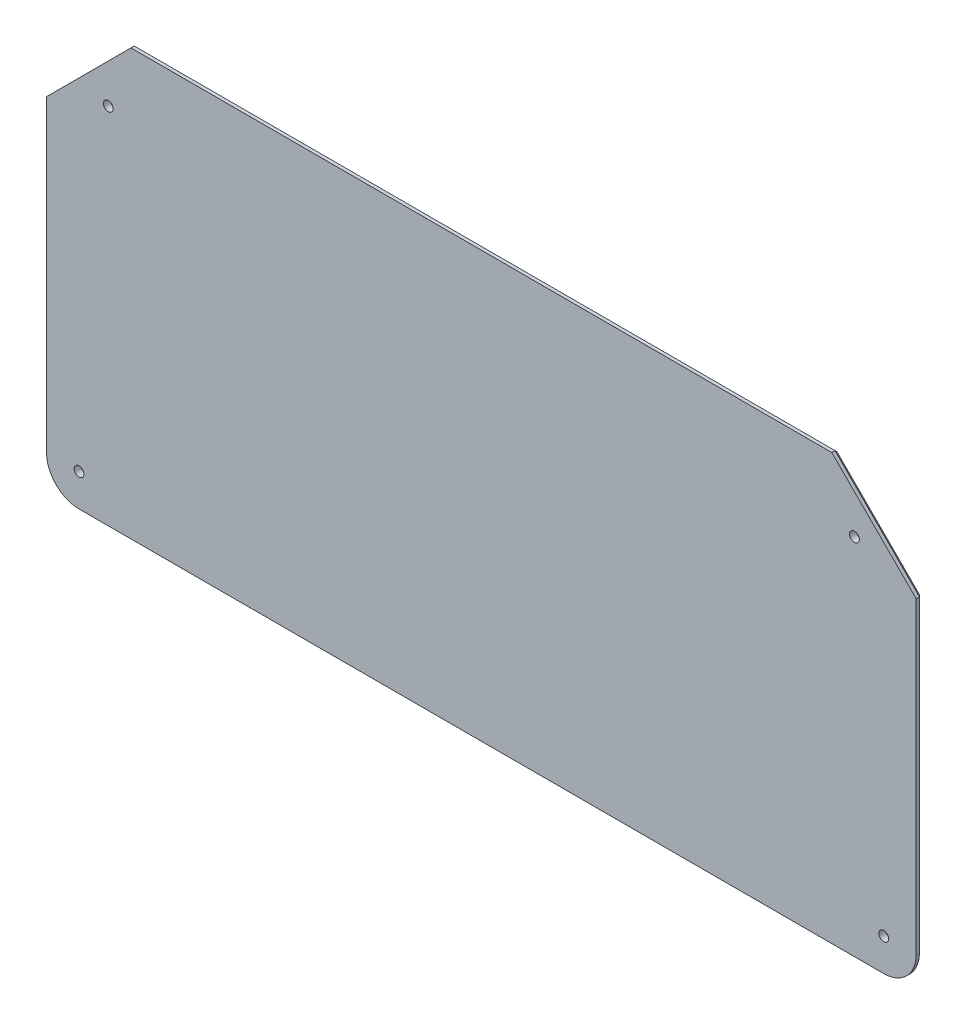
SolidWorks part; units mm, degrees
ref_plane "Front Plane" through (0, 0, 0) normal (0, 0, 1) x (1, 0, 0)
ref_plane "Top Plane" through (0, 0, 0) normal (0, 1, 0) x (1, 0, 0)
ref_plane "Right Plane" through (0, 0, 0) normal (1, 0, 0) x (0, 0, -1)
sketch "Sketch1" plane through (0, 0, 0) normal (0, 0, 1) x (1, 0, 0)
  line L0 (157.8919, 26.2701) -> (191.7747, 29.0915)
  line L1 (157.8919, 26.2701) -> (191.7747, 26.2701)
  line L2 (157.8919, 26.2701) -> (157.8919, 29.0915)
  line L3 (157.8919, 29.0915) -> (191.7747, 29.0915)
  line L4 (191.7747, 26.2701) -> (191.7747, 29.0915)
  line L5 (123.8919, 26.2701) -> (90.0092, 26.2701)
  line L6 (123.8919, 26.2701) -> (123.8919, 29.0915)
  line L7 (123.8919, 29.0915) -> (90.0092, 29.0915)
  line L8 (90.0092, 26.2701) -> (90.0092, 29.0915)
  line L9 (90.0092, 29.0915) -> (123.8919, 26.2701)
  line L10 (168.0919, 58.3601) -> (194.8735, 70.7292)
  line L11 (168.0919, 58.3601) -> (194.8735, 58.3601)
  line L12 (168.0919, 58.3601) -> (168.0919, 70.7292)
  line L13 (168.0919, 70.7292) -> (194.8735, 70.7292)
  line L14 (194.8735, 58.3601) -> (194.8735, 70.7292)
  line L15 (194.8735, 70.7292) -> (224.3587, 70.7292)
  line L16 (194.8735, 70.7292) -> (194.8735, 69.7923)
  line L17 (194.8735, 69.7923) -> (224.3587, 69.7923)
  line L18 (224.3587, 70.7292) -> (224.3587, 69.7923)
  line L19 (224.3587, 69.7923) -> (253.5106, 69.7923)
  line L20 (224.3587, 69.7923) -> (224.3587, 65.2742)
  line L21 (224.3587, 65.2742) -> (253.5106, 65.2742)
  line L22 (253.5106, 69.7923) -> (253.5106, 65.2742)
  line L23 (224.3587, 69.7923) -> (194.8735, 70.7292)
  line L24 (253.5106, 65.2742) -> (224.3587, 69.7923)
  line L25 (170.7502, 87.7401) -> (168.0919, 58.3601)
  line L26 (168.0919, 58.3601) -> (170.7502, 58.3601)
  line L27 (168.0919, 58.3601) -> (168.0919, 87.7401)
  line L28 (168.0919, 87.7401) -> (170.7502, 87.7401)
  line L29 (170.7502, 58.3601) -> (170.7502, 87.7401)
  line L30 (52.9966, 89.4705) -> (24.4119, 82.1791)
  line L31 (24.4119, 82.1791) -> (52.9966, 82.1791)
  line L32 (24.4119, 82.1791) -> (24.4119, 89.4705)
  line L33 (24.4119, 89.4705) -> (52.9966, 89.4705)
  line L34 (52.9966, 82.1791) -> (52.9966, 89.4705)
  line L35 (82.4966, 89.4705) -> (109.0019, 89.4705)
  line L36 (82.4966, 89.4705) -> (82.4966, 76.5201)
  line L37 (82.4966, 76.5201) -> (109.0019, 76.5201)
  line L38 (109.0019, 89.4705) -> (109.0019, 76.5201)
  line L39 (92.4554, 117.2387) -> (82.4966, 117.2387)
  line L40 (92.4554, 117.2387) -> (92.4554, 89.4705)
  line L41 (92.4554, 89.4705) -> (82.4966, 89.4705)
  line L42 (82.4966, 117.2387) -> (82.4966, 89.4705)
  line L43 (92.4554, 117.2387) -> (82.4966, 89.4705)
  line L44 (109.0019, 76.5201) -> (82.4966, 89.4705)
  circle A0 centre (123.8919, 26.2701) radius 14.25
  circle A1 centre (157.8919, 26.2701) radius 14.25
  circle A2 centre (90.0092, 29.0915) radius 14.25
  circle A3 centre (191.7747, 29.0915) radius 14.25
  circle A4 centre (82.4966, 89.4705) radius 11.25
  circle A5 centre (92.4554, 117.2387) radius 11.25
  circle A6 centre (52.9966, 89.4705) radius 11.25
  circle A7 centre (109.0019, 76.5201) radius 11.25
  circle A8 centre (24.4119, 82.1791) radius 11.25
  circle A9 centre (170.7502, 87.7401) radius 11.25
  circle A10 centre (168.0919, 58.3601) radius 11.25
  circle A11 centre (197.5318, 100.1092) radius 11.25
  circle A12 centre (194.8735, 70.7292) radius 11.25
  circle A13 centre (227.0169, 99.1723) radius 11.25
  circle A14 centre (224.3587, 69.7923) radius 11.25
  circle A15 centre (256.1689, 94.6541) radius 11.25
  circle A16 centre (253.5106, 65.2742) radius 11.25
  circle A17 centre (24.4119, 82.1791) radius 12
  circle A18 centre (52.9966, 89.4705) radius 12
  circle A19 centre (92.4554, 117.2387) radius 12
  circle A20 centre (82.4966, 89.4705) radius 12
  circle A21 centre (109.0019, 76.5201) radius 12
  circle A22 centre (168.0919, 58.3601) radius 12
  circle A23 centre (194.8735, 70.7292) radius 12
  circle A24 centre (224.3587, 69.7923) radius 12
  circle A25 centre (253.5106, 65.2742) radius 12
  circle A26 centre (256.1689, 94.6541) radius 12
  circle A27 centre (227.0169, 99.1723) radius 12
  circle A28 centre (197.5318, 100.1092) radius 12
  circle A29 centre (170.7502, 87.7401) radius 12
  circle A30 centre (191.7747, 29.0915) radius 15
  circle A31 centre (157.8919, 26.2701) radius 15
  circle A32 centre (123.8919, 26.2701) radius 15
  circle A33 centre (90.0092, 29.0915) radius 15
  circle A34 centre (173.429, 117.1182) radius 11.25
  circle A35 centre (173.429, 117.1182) radius 12
  dimension "D1" = 28.5
  dimension "D2" = 22.5
  dimension "D3" = 0.75
  dimension "D4" = 0.75
  dimension "D34" = 34
  dimension "D5" = 29.5
  dimension "D6" = 29.5
  dimension "D7" = 29.5
  dimension "D8" = 29.5
  dimension "D9" = 29.5
  dimension "D10" = 29.5
  dimension "D11" = 29.5
  dimension "D12" = 29.5
  dimension "D13" = 29.5
  dimension "D14" = 29.5
  dimension "D15" = 29.5
  dimension "D16" = 29.5
  dimension "D17" = 29.5
  dimension "D18" = 29.5
  dimension "D19" = 34
  dimension "D20" = 34
  dimension "D21" = 32.09
  dimension "D22" = 10.2
  dimension "D23" = 4.76
  dimension "D24" = 4.76
  dimension "D25" = 24.79
  dimension "D26" = 1.82
  dimension "D27" = 8.81
  dimension "D28" = 84.83
  dimension "D29" = 75.69
  dimension "D30" = 70.27
  dimension "D31" = 26.04
  dimension "D32" = 14.89
  dimension "D33" = 50.25
  dimension "D35" = 29.5
  dimension "D36" = 29.5
sketch "Sketch4" plane through (-30.2083, 20.075, 0) normal (0, 0, 1) x (0.9781, -0.2079, 0)
  line L0 (86.1706, 94.1917) -> (105.2206, 75.1417)
  line L1 (67.1206, 94.1917) -> (86.1706, 94.1917)
  line L2 (67.1206, 94.1917) -> (67.1206, 75.1417)
  line L3 (67.1206, 75.1417) -> (86.1706, 75.1417)
  line L4 (86.1706, 94.1917) -> (86.1706, 75.1417)
  line L5 (86.1706, 94.1917) -> (105.2206, 94.1917)
  line L6 (86.1706, 94.1917) -> (86.1706, 75.1417)
  line L7 (86.1706, 75.1417) -> (105.2206, 75.1417)
  line L8 (105.2206, 94.1917) -> (105.2206, 75.1417)
  line L9 (105.2206, 94.1917) -> (124.2706, 94.1917)
  line L10 (105.2206, 94.1917) -> (105.2206, 75.1417)
  line L11 (105.2206, 75.1417) -> (124.2706, 75.1417)
  line L12 (124.2706, 94.1917) -> (124.2706, 75.1417)
  line L13 (86.1706, 94.1917) -> (105.2206, 94.1917)
  line L14 (86.1706, 94.1917) -> (86.1706, 113.2417)
  line L15 (86.1706, 113.2417) -> (105.2206, 113.2417)
  line L16 (105.2206, 94.1917) -> (105.2206, 113.2417)
  line L17 (66.9585, 85.1784) -> (124.4326, 84.1551)
  point P14 (95.6956, 84.6667)
  point P15 (95.6956, 84.6667)
  dimension "D1" = 19.05
sketch "Sketch9" plane through (0, 0, 0) normal (0, 0, 1) x (1, 0, 0)
  line L1 (17.3619, 89.2291) -> (31.4619, 89.2291)
  line L2 (17.3619, 89.2291) -> (17.3619, 75.1291)
  line L3 (17.3619, 75.1291) -> (31.4619, 75.1291)
  line L4 (31.4619, 89.2291) -> (31.4619, 75.1291)
  line L5 (45.9466, 96.5205) -> (60.0466, 96.5205)
  line L6 (45.9466, 96.5205) -> (45.9466, 82.4205)
  line L7 (45.9466, 82.4205) -> (60.0466, 82.4205)
  line L8 (60.0466, 96.5205) -> (60.0466, 82.4205)
  line L9 (75.4466, 96.5205) -> (89.5466, 96.5205)
  line L10 (75.4466, 96.5205) -> (75.4466, 82.4205)
  line L11 (75.4466, 82.4205) -> (89.5466, 82.4205)
  line L12 (89.5466, 96.5205) -> (89.5466, 82.4205)
  line L13 (101.9519, 83.5701) -> (116.0519, 83.5701)
  line L14 (101.9519, 83.5701) -> (101.9519, 69.4701)
  line L15 (101.9519, 69.4701) -> (116.0519, 69.4701)
  line L16 (116.0519, 83.5701) -> (116.0519, 69.4701)
  line L17 (85.4054, 124.2887) -> (99.5054, 124.2887)
  line L18 (85.4054, 124.2887) -> (85.4054, 110.1887)
  line L19 (85.4054, 110.1887) -> (99.5054, 110.1887)
  line L20 (99.5054, 124.2887) -> (99.5054, 110.1887)
  line L21 (82.9592, 36.1415) -> (97.0592, 36.1415)
  line L22 (82.9592, 36.1415) -> (82.9592, 22.0415)
  line L23 (82.9592, 22.0415) -> (97.0592, 22.0415)
  line L24 (97.0592, 36.1415) -> (97.0592, 22.0415)
  line L25 (116.8419, 33.3201) -> (130.9419, 33.3201)
  line L26 (116.8419, 33.3201) -> (116.8419, 19.2201)
  line L27 (116.8419, 19.2201) -> (130.9419, 19.2201)
  line L28 (130.9419, 33.3201) -> (130.9419, 19.2201)
  line L29 (150.8419, 33.3201) -> (164.9419, 33.3201)
  line L30 (150.8419, 33.3201) -> (150.8419, 19.2201)
  line L31 (150.8419, 19.2201) -> (164.9419, 19.2201)
  line L32 (164.9419, 33.3201) -> (164.9419, 19.2201)
  line L33 (184.7247, 36.1415) -> (198.8247, 36.1415)
  line L34 (184.7247, 36.1415) -> (184.7247, 22.0415)
  line L35 (184.7247, 22.0415) -> (198.8247, 22.0415)
  line L36 (198.8247, 36.1415) -> (198.8247, 22.0415)
  line L37 (260.5606, 58.2242) -> (246.4606, 58.2242)
  line L38 (260.5606, 58.2242) -> (260.5606, 72.3242)
  line L39 (260.5606, 72.3242) -> (246.4606, 72.3242)
  line L40 (246.4606, 58.2242) -> (246.4606, 72.3242)
  line L41 (217.3087, 76.8423) -> (231.4087, 76.8423)
  line L42 (217.3087, 76.8423) -> (217.3087, 62.7423)
  line L43 (217.3087, 62.7423) -> (231.4087, 62.7423)
  line L44 (231.4087, 76.8423) -> (231.4087, 62.7423)
  line L45 (187.8235, 77.7792) -> (201.9235, 77.7792)
  line L46 (187.8235, 77.7792) -> (187.8235, 63.6792)
  line L47 (187.8235, 63.6792) -> (201.9235, 63.6792)
  line L48 (201.9235, 77.7792) -> (201.9235, 63.6792)
  line L49 (161.0419, 65.4101) -> (175.1419, 65.4101)
  line L50 (161.0419, 65.4101) -> (161.0419, 51.3101)
  line L51 (161.0419, 51.3101) -> (175.1419, 51.3101)
  line L52 (175.1419, 65.4101) -> (175.1419, 51.3101)
  line L53 (163.7002, 94.7901) -> (177.8002, 94.7901)
  line L54 (163.7002, 94.7901) -> (163.7002, 80.6901)
  line L55 (163.7002, 80.6901) -> (177.8002, 80.6901)
  line L56 (177.8002, 94.7901) -> (177.8002, 80.6901)
  line L57 (190.4818, 107.1592) -> (204.5818, 107.1592)
  line L58 (190.4818, 107.1592) -> (190.4818, 93.0592)
  line L59 (190.4818, 93.0592) -> (204.5818, 93.0592)
  line L60 (204.5818, 107.1592) -> (204.5818, 93.0592)
  line L61 (219.9669, 106.2223) -> (234.0669, 106.2223)
  line L62 (219.9669, 106.2223) -> (219.9669, 92.1223)
  line L63 (219.9669, 92.1223) -> (234.0669, 92.1223)
  line L64 (234.0669, 106.2223) -> (234.0669, 92.1223)
  line L65 (249.1189, 101.7041) -> (263.2189, 101.7041)
  line L66 (249.1189, 101.7041) -> (249.1189, 87.6041)
  line L67 (249.1189, 87.6041) -> (263.2189, 87.6041)
  line L68 (263.2189, 101.7041) -> (263.2189, 87.6041)
  line L69 (166.379, 124.1682) -> (180.479, 124.1682)
  line L70 (166.379, 124.1682) -> (166.379, 110.0682)
  line L71 (166.379, 110.0682) -> (180.479, 110.0682)
  line L72 (180.479, 124.1682) -> (180.479, 110.0682)
  point P72 (24.4119, 89.2291)
  point P74 (52.9966, 96.5205)
  point P76 (82.4966, 96.5205)
  point P78 (92.4554, 124.2887)
  point P80 (109.0019, 83.5701)
  point P82 (90.0092, 36.1415)
  point P84 (123.8919, 33.3201)
  point P86 (157.8919, 33.3201)
  point P88 (191.7747, 36.1415)
  point P90 (168.0919, 65.4101)
  point P92 (170.7502, 94.7901)
  point P94 (173.429, 124.1682)
  point P96 (197.5318, 107.1592)
  point P98 (227.0169, 106.2223)
  point P100 (256.1689, 101.7041)
  point P102 (194.8735, 77.7792)
  point P104 (224.3587, 76.8423)
  point P106 (253.5106, 72.3242)
  point P108 (17.3619, 82.1791)
  point P109 (45.9466, 89.4705)
  point P110 (75.4466, 89.4705)
  point P111 (101.9519, 76.5201)
  point P112 (85.4054, 117.2387)
  point P113 (82.9592, 29.0915)
  point P114 (116.8419, 26.2701)
  point P115 (150.8419, 26.2701)
  point P116 (184.7247, 29.0915)
  point P118 (161.0419, 58.3601)
  point P119 (187.8235, 70.7292)
  point P120 (217.3087, 69.7923)
  point P121 (246.4606, 65.2742)
  point P122 (163.7002, 87.7401)
  point P123 (190.4818, 100.1092)
  point P124 (219.9669, 99.1723)
  point P125 (249.1189, 94.6541)
  point P126 (166.379, 117.1182)
  dimension "D1" = 14.1
sketch "Sketch10" plane through (-22.0981, 19.3454, 0) normal (0, 0, 1) x (0.9781, -0.2079, 0)
  line L1 (61.5108, 90.7441) -> (75.6108, 90.7441)
  line L2 (61.5108, 90.7441) -> (61.5108, 76.6441)
  line L3 (61.5108, 76.6441) -> (75.6108, 76.6441)
  line L4 (75.6108, 90.7441) -> (75.6108, 76.6441)
  line L5 (80.5608, 90.7441) -> (94.6608, 90.7441)
  line L6 (80.5608, 90.7441) -> (80.5608, 76.6441)
  line L7 (80.5608, 76.6441) -> (94.6608, 76.6441)
  line L8 (94.6608, 90.7441) -> (94.6608, 76.6441)
  line L9 (99.6108, 90.7441) -> (113.7108, 90.7441)
  line L10 (99.6108, 90.7441) -> (99.6108, 76.6441)
  line L11 (99.6108, 76.6441) -> (113.7108, 76.6441)
  line L12 (113.7108, 90.7441) -> (113.7108, 76.6441)
  line L13 (80.5608, 109.7941) -> (94.6608, 109.7941)
  line L14 (80.5608, 109.7941) -> (80.5608, 95.6941)
  line L15 (80.5608, 95.6941) -> (94.6608, 95.6941)
  line L16 (94.6608, 109.7941) -> (94.6608, 95.6941)
  line L17 (50.5121, 89.6359) -> (53.4436, 75.8441) construction
  line L18 (59.0358, 93.2191) -> (78.0858, 93.2191) construction
  line L19 (78.0858, 112.2691) -> (97.1358, 112.2691) construction
  line L20 (97.1358, 93.2191) -> (116.1858, 93.2191) construction
  line L21 (78.0858, 93.2191) -> (78.0858, 112.2691) construction
  line L23 (59.0358, 93.2191) -> (59.0358, 74.1691) construction
  point P16 (75.6108, 83.6941)
  point P17 (94.6608, 83.6941)
  point P18 (113.7108, 83.6941)
  point P19 (87.6108, 90.7441)
  point P20 (87.6108, 109.7941)
  point P23 (68.5608, 90.7441)
  point P26 (68.5608, 93.2191)
  point P29 (87.6108, 112.2691)
  point P30 (106.6608, 90.7441)
  point P33 (106.6608, 93.2191)
  point P34 (80.5608, 102.7441)
  point P37 (78.0858, 102.7441)
  point P42 (59.0358, 83.6941)
  point P43 (61.5108, 83.6941)
sketch "Sketch14" plane through (0, 0, 0) normal (0, 0, 1) x (1, 0, 0)
  line L0 (165.1144, 80.6901) -> (163.7002, 82.1043)
  line L1 (163.7002, 93.3758) -> (165.1144, 94.7901)
  line L2 (177.8002, 93.3758) -> (176.386, 94.7901)
  line L3 (179.0648, 110.0682) -> (180.479, 111.4824)
  line L4 (166.379, 111.4824) -> (167.7932, 110.0682)
  line L5 (166.379, 122.754) -> (167.7932, 124.1682)
  line L6 (179.0648, 124.1682) -> (180.479, 122.754)
  line L7 (203.1676, 93.0592) -> (204.5818, 94.4734)
  line L8 (17.3619, 89.2291) -> (17.3619, 75.1291) construction
  line L9 (17.3619, 89.2291) -> (31.4619, 89.2291) construction
  line L10 (17.3619, 87.8149) -> (18.7761, 89.2291)
  line L11 (17.3619, 75.1291) -> (31.4619, 75.1291) construction
  line L12 (31.4619, 89.2291) -> (31.4619, 75.1291) construction
  line L13 (45.9466, 96.5205) -> (60.0466, 96.5205) construction
  line L14 (60.0466, 96.5205) -> (60.0466, 82.4205) construction
  line L15 (45.9466, 96.5205) -> (45.9466, 82.4205) construction
  line L16 (45.9466, 82.4205) -> (60.0466, 82.4205) construction
  line L17 (85.4054, 124.2887) -> (85.4054, 110.1887) construction
  line L18 (85.4054, 124.2887) -> (99.5054, 124.2887) construction
  line L19 (99.5054, 124.2887) -> (99.5054, 110.1887) construction
  line L20 (85.4054, 110.1887) -> (99.5054, 110.1887) construction
  line L21 (101.9519, 83.5701) -> (101.9519, 69.4701) construction
  line L22 (101.9519, 83.5701) -> (116.0519, 83.5701) construction
  line L23 (116.0519, 83.5701) -> (116.0519, 69.4701) construction
  line L24 (101.9519, 69.4701) -> (116.0519, 69.4701) construction
  line L25 (91.2712, 73.6044) -> (105.0631, 70.6729) construction
  line L26 (107.9947, 84.4647) -> (105.0631, 70.6729) construction
  line L27 (94.2028, 87.3963) -> (107.9947, 84.4647) construction
  line L28 (94.2028, 87.3963) -> (91.2712, 73.6044) construction
  line L29 (72.6375, 77.5651) -> (86.4294, 74.6336) construction
  line L30 (89.361, 88.4255) -> (86.4294, 74.6336) construction
  line L31 (75.5691, 91.357) -> (89.361, 88.4255) construction
  line L32 (75.5691, 91.357) -> (72.6375, 77.5651) construction
  line L33 (56.9354, 95.3177) -> (54.0038, 81.5259) construction
  line L34 (56.9354, 95.3177) -> (70.7273, 92.3862) construction
  line L35 (70.7273, 92.3862) -> (67.7957, 78.5943) construction
  line L36 (54.0038, 81.5259) -> (67.7957, 78.5943) construction
  line L37 (76.5983, 96.1988) -> (90.3901, 93.2673) construction
  line L38 (93.3217, 107.0592) -> (90.3901, 93.2673) construction
  line L39 (79.5298, 109.9907) -> (76.5983, 96.1988) construction
  line L40 (79.5298, 109.9907) -> (93.3217, 107.0592) construction
  line L41 (82.9592, 36.1415) -> (82.9592, 22.0415) construction
  line L42 (82.9592, 36.1415) -> (97.0592, 36.1415) construction
  line L43 (82.9592, 22.0415) -> (97.0592, 22.0415) construction
  line L44 (97.0592, 36.1415) -> (97.0592, 22.0415) construction
  line L45 (116.8419, 33.3201) -> (116.8419, 19.2201) construction
  line L46 (116.8419, 33.3201) -> (130.9419, 33.3201) construction
  line L47 (116.8419, 19.2201) -> (130.9419, 19.2201) construction
  line L48 (130.9419, 33.3201) -> (130.9419, 19.2201) construction
  line L49 (150.8419, 33.3201) -> (150.8419, 19.2201) construction
  line L50 (150.8419, 33.3201) -> (164.9419, 33.3201) construction
  line L51 (164.9419, 33.3201) -> (164.9419, 19.2201) construction
  line L52 (150.8419, 19.2201) -> (164.9419, 19.2201) construction
  line L53 (184.7247, 36.1415) -> (184.7247, 22.0415) construction
  line L54 (184.7247, 22.0415) -> (198.8247, 22.0415) construction
  line L55 (198.8247, 36.1415) -> (198.8247, 22.0415) construction
  line L56 (184.7247, 36.1415) -> (198.8247, 36.1415) construction
  line L57 (161.0419, 65.4101) -> (175.1419, 65.4101) construction
  line L58 (175.1419, 65.4101) -> (175.1419, 51.3101) construction
  line L59 (161.0419, 51.3101) -> (175.1419, 51.3101) construction
  line L60 (161.0419, 65.4101) -> (161.0419, 51.3101) construction
  line L61 (187.8235, 77.7792) -> (187.8235, 63.6792) construction
  line L62 (187.8235, 77.7792) -> (201.9235, 77.7792) construction
  line L63 (187.8235, 63.6792) -> (201.9235, 63.6792) construction
  line L64 (201.9235, 77.7792) -> (201.9235, 63.6792) construction
  line L65 (217.3087, 76.8423) -> (217.3087, 62.7423) construction
  line L66 (217.3087, 76.8423) -> (231.4087, 76.8423) construction
  line L67 (231.4087, 76.8423) -> (231.4087, 62.7423) construction
  line L68 (217.3087, 62.7423) -> (231.4087, 62.7423) construction
  line L69 (260.5606, 58.2242) -> (246.4606, 58.2242) construction
  line L70 (260.5606, 58.2242) -> (260.5606, 72.3242) construction
  line L71 (246.4606, 58.2242) -> (246.4606, 72.3242) construction
  line L72 (260.5606, 72.3242) -> (246.4606, 72.3242) construction
  line L73 (249.1189, 101.7041) -> (263.2189, 101.7041) construction
  line L74 (263.2189, 101.7041) -> (263.2189, 87.6041) construction
  line L75 (249.1189, 87.6041) -> (263.2189, 87.6041) construction
  line L76 (249.1189, 101.7041) -> (249.1189, 87.6041) construction
  line L77 (219.9669, 106.2223) -> (219.9669, 92.1223) construction
  line L78 (219.9669, 106.2223) -> (234.0669, 106.2223) construction
  line L79 (234.0669, 106.2223) -> (234.0669, 92.1223) construction
  line L80 (219.9669, 92.1223) -> (234.0669, 92.1223) construction
  line L81 (190.4818, 107.1592) -> (204.5818, 107.1592) construction
  line L82 (204.5818, 107.1592) -> (204.5818, 93.0592) construction
  line L83 (190.4818, 93.0592) -> (204.5818, 93.0592) construction
  line L84 (190.4818, 107.1592) -> (190.4818, 93.0592) construction
  line L85 (163.7002, 94.7901) -> (177.8002, 94.7901) construction
  line L86 (177.8002, 94.7901) -> (177.8002, 80.6901) construction
  line L87 (163.7002, 80.6901) -> (177.8002, 80.6901) construction
  line L88 (163.7002, 94.7901) -> (163.7002, 80.6901) construction
  line L89 (180.479, 124.1682) -> (180.479, 110.0682) construction
  line L90 (166.379, 110.0682) -> (180.479, 110.0682) construction
  line L91 (166.379, 124.1682) -> (166.379, 110.0682) construction
  line L92 (166.379, 124.1682) -> (180.479, 124.1682) construction
  line L93 (17.3619, 76.5433) -> (18.7761, 75.1291)
  line L94 (30.0477, 75.1291) -> (31.4619, 76.5433)
  line L95 (31.4619, 87.8149) -> (30.0477, 89.2291)
  line L96 (45.9466, 95.1063) -> (47.3608, 96.5205)
  line L97 (45.9466, 83.8347) -> (47.3608, 82.4205)
  line L98 (54.2979, 82.9092) -> (55.3871, 81.2318)
  line L99 (58.6323, 82.4205) -> (60.0466, 83.8347)
  line L100 (56.6413, 93.9344) -> (58.3187, 95.0237)
  line L101 (58.6323, 96.5205) -> (60.0466, 95.1063)
  line L102 (69.3439, 92.6802) -> (70.4332, 91.0029)
  line L103 (68.0897, 79.9776) -> (66.4124, 78.8883)
  line L104 (75.2751, 89.9737) -> (76.9524, 91.063)
  line L105 (72.9316, 78.9484) -> (74.0208, 77.2711)
  line L106 (85.0461, 74.9276) -> (86.7234, 76.0169)
  line L107 (89.0669, 87.0421) -> (87.9777, 88.7195)
  line L108 (89.0068, 93.5613) -> (90.6842, 94.6506)
  line L109 (76.8923, 97.5822) -> (77.9816, 95.9048)
  line L110 (91.9384, 107.3532) -> (93.0277, 105.6759)
  line L111 (79.2358, 108.6074) -> (80.9131, 109.6967)
  line L112 (85.4054, 111.6029) -> (86.8196, 110.1887)
  line L113 (98.0912, 110.1887) -> (99.5054, 111.6029)
  line L114 (98.0912, 124.2887) -> (99.5054, 122.8745)
  line L115 (85.4054, 122.8745) -> (86.8196, 124.2887)
  line L116 (93.9088, 86.013) -> (95.5861, 87.1023)
  line L117 (91.5653, 74.9877) -> (92.6546, 73.3104)
  line L118 (103.6798, 70.9669) -> (105.3572, 72.0562)
  line L119 (106.6114, 84.7588) -> (107.7006, 83.0814)
  line L120 (101.9519, 82.1559) -> (103.3662, 83.5701)
  line L121 (101.9519, 70.8843) -> (103.3662, 69.4701)
  line L122 (114.6377, 69.4701) -> (116.0519, 70.8843)
  line L123 (116.0519, 82.1559) -> (114.6377, 83.5701)
  line L124 (82.9592, 34.7272) -> (84.3734, 36.1415)
  line L125 (82.9592, 23.4557) -> (84.3734, 22.0415)
  line L126 (95.645, 22.0415) -> (97.0592, 23.4557)
  line L127 (97.0592, 34.7272) -> (95.645, 36.1415)
  line L128 (116.8419, 31.9059) -> (118.2562, 33.3201)
  line L129 (116.8419, 20.6343) -> (118.2562, 19.2201)
  line L130 (129.5277, 19.2201) -> (130.9419, 20.6343)
  line L131 (130.9419, 31.9059) -> (129.5277, 33.3201)
  line L132 (150.8419, 31.9059) -> (152.2562, 33.3201)
  line L133 (150.8419, 20.6343) -> (152.2562, 19.2201)
  line L134 (163.5277, 19.2201) -> (164.9419, 20.6343)
  line L135 (164.9419, 31.9059) -> (163.5277, 33.3201)
  line L136 (184.7247, 34.7272) -> (186.1389, 36.1415)
  line L137 (184.7247, 23.4557) -> (186.1389, 22.0415)
  line L138 (197.4105, 22.0415) -> (198.8247, 23.4557)
  line L139 (198.8247, 34.7272) -> (197.4105, 36.1415)
  line L140 (173.7277, 51.3101) -> (175.1419, 52.7243)
  line L141 (161.0419, 52.7243) -> (162.4562, 51.3101)
  line L142 (161.0419, 63.9959) -> (162.4562, 65.4101)
  line L143 (173.7277, 65.4101) -> (175.1419, 63.9959)
  line L144 (187.8235, 65.0934) -> (189.2378, 63.6792)
  line L145 (200.5093, 63.6792) -> (201.9235, 65.0934)
  line L146 (200.5093, 77.7792) -> (201.9235, 76.365)
  line L147 (187.8235, 76.365) -> (189.2378, 77.7792)
  line L148 (176.386, 80.6901) -> (177.8002, 82.1043)
  line L149 (204.5818, 105.745) -> (203.1676, 107.1592)
  line L150 (191.896, 107.1592) -> (190.4818, 105.745)
  line L151 (190.4818, 94.4734) -> (191.896, 93.0592)
  line L152 (219.9669, 104.8081) -> (221.3812, 106.2223)
  line L153 (232.6527, 106.2223) -> (234.0669, 104.8081)
  line L154 (234.0669, 93.5365) -> (232.6527, 92.1223)
  line L155 (219.9669, 93.5365) -> (221.3812, 92.1223)
  line L156 (229.9944, 76.8423) -> (231.4087, 75.4281)
  line L157 (217.3087, 75.4281) -> (218.7229, 76.8423)
  line L158 (217.3087, 64.1565) -> (218.7229, 62.7423)
  line L159 (229.9944, 62.7423) -> (231.4087, 64.1565)
  line L160 (259.1464, 72.3242) -> (260.5606, 70.9099)
  line L161 (246.4606, 70.9099) -> (247.8748, 72.3242)
  line L162 (259.1464, 58.2242) -> (260.5606, 59.6384)
  line L163 (247.8748, 58.2242) -> (246.4606, 59.6384)
  line L164 (261.8047, 87.6041) -> (263.2189, 89.0183)
  line L165 (249.1189, 89.0183) -> (250.5331, 87.6041)
  line L166 (249.1189, 100.2899) -> (250.5331, 101.7041)
  line L167 (261.8047, 101.7041) -> (263.2189, 100.2899)
  line L168 (75.4466, 96.5205) -> (75.4466, 82.4205) construction
  line L169 (75.4466, 96.5205) -> (89.5466, 96.5205) construction
  line L170 (89.5466, 96.5205) -> (89.5466, 82.4205) construction
  line L171 (75.4466, 82.4205) -> (89.5466, 82.4205) construction
  line L172 (76.8608, 96.5205) -> (75.4466, 95.1063)
  line L173 (88.1323, 96.5205) -> (89.5466, 95.1063)
  line L174 (89.5466, 83.8347) -> (88.1323, 82.4205)
  line L175 (75.4466, 83.8347) -> (76.8608, 82.4205)
  arc A0 (17.3619, 87.8149) -> (18.7761, 89.2291) centre (18.069, 88.522) cw
  arc A1 (18.7761, 75.1291) -> (17.3619, 76.5433) centre (18.069, 75.8362) cw
  arc A2 (31.4619, 76.5433) -> (30.0477, 75.1291) centre (30.7548, 75.8362) cw
  arc A3 (30.0477, 89.2291) -> (31.4619, 87.8149) centre (30.7548, 88.522) cw
  arc A4 (58.6323, 96.5205) -> (60.0466, 95.1063) centre (59.3394, 95.8134) cw
  arc A5 (45.9466, 95.1063) -> (47.3608, 96.5205) centre (46.6537, 95.8134) cw
  arc A6 (47.3608, 82.4205) -> (45.9466, 83.8347) centre (46.6537, 83.1276) cw
  arc A7 (60.0466, 83.8347) -> (58.6323, 82.4205) centre (59.3394, 83.1276) cw
  arc A8 (85.4054, 122.8745) -> (86.8196, 124.2887) centre (86.1125, 123.5816) cw
  arc A9 (98.0912, 124.2887) -> (99.5054, 122.8745) centre (98.7983, 123.5816) cw
  arc A10 (99.5054, 111.6029) -> (98.0912, 110.1887) centre (98.7983, 110.8958) cw
  arc A11 (85.4054, 111.6029) -> (86.8196, 110.1887) centre (86.1125, 110.8958) ccw
  arc A12 (101.9519, 82.1559) -> (103.3662, 83.5701) centre (102.6591, 82.863) cw
  arc A13 (114.6377, 83.5701) -> (116.0519, 82.1559) centre (115.3448, 82.863) cw
  arc A14 (116.0519, 70.8843) -> (114.6377, 69.4701) centre (115.3448, 70.1772) cw
  arc A15 (101.9519, 70.8843) -> (103.3662, 69.4701) centre (102.6591, 70.1772) ccw
  arc A16 (103.6798, 70.9669) -> (105.3572, 72.0562) centre (104.5185, 71.5115) ccw
  arc A17 (106.6114, 84.7588) -> (107.7006, 83.0814) centre (107.156, 83.9201) cw
  arc A18 (93.9088, 86.013) -> (95.5861, 87.1023) centre (94.7474, 86.5576) cw
  arc A19 (91.5653, 74.9877) -> (92.6546, 73.3104) centre (92.1099, 74.1491) ccw
  arc A20 (85.0461, 74.9276) -> (86.7234, 76.0169) centre (85.8848, 75.4722) ccw
  arc A21 (87.9777, 88.7195) -> (89.0669, 87.0421) centre (88.5223, 87.8808) cw
  arc A22 (75.2751, 89.9737) -> (76.9524, 91.063) centre (76.1137, 90.5183) cw
  arc A23 (72.9316, 78.9484) -> (74.0208, 77.2711) centre (73.4762, 78.1098) ccw
  arc A24 (56.6413, 93.9344) -> (58.3187, 95.0237) centre (57.48, 94.4791) cw
  arc A25 (69.3439, 92.6802) -> (70.4332, 91.0029) centre (69.8886, 91.8415) cw
  arc A26 (68.0897, 79.9776) -> (66.4124, 78.8883) centre (67.2511, 79.433) cw
  arc A27 (54.2979, 82.9092) -> (55.3871, 81.2318) centre (54.8425, 82.0705) ccw
  arc A28 (89.0068, 93.5613) -> (90.6842, 94.6506) centre (89.8455, 94.106) ccw
  arc A29 (76.8923, 97.5822) -> (77.9816, 95.9048) centre (77.4369, 96.7435) ccw
  arc A30 (79.2358, 108.6074) -> (80.9131, 109.6967) centre (80.0744, 109.1521) cw
  arc A31 (91.9384, 107.3532) -> (93.0277, 105.6759) centre (92.483, 106.5145) cw
  arc A32 (82.9592, 34.7272) -> (84.3734, 36.1415) centre (83.6663, 35.4344) cw
  arc A33 (82.9592, 23.4557) -> (84.3734, 22.0415) centre (83.6663, 22.7486) ccw
  arc A34 (95.645, 22.0415) -> (97.0592, 23.4557) centre (96.3521, 22.7486) ccw
  arc A35 (95.645, 36.1415) -> (97.0592, 34.7272) centre (96.3521, 35.4344) cw
  arc A36 (116.8419, 31.9059) -> (118.2562, 33.3201) centre (117.5491, 32.613) cw
  arc A37 (116.8419, 20.6343) -> (118.2562, 19.2201) centre (117.5491, 19.9272) ccw
  arc A38 (129.5277, 19.2201) -> (130.9419, 20.6343) centre (130.2348, 19.9272) ccw
  arc A39 (129.5277, 33.3201) -> (130.9419, 31.9059) centre (130.2348, 32.613) cw
  arc A40 (150.8419, 31.9059) -> (152.2562, 33.3201) centre (151.5491, 32.613) cw
  arc A41 (163.5277, 33.3201) -> (164.9419, 31.9059) centre (164.2348, 32.613) cw
  arc A42 (164.9419, 20.6343) -> (163.5277, 19.2201) centre (164.2348, 19.9272) cw
  arc A43 (150.8419, 20.6343) -> (152.2562, 19.2201) centre (151.5491, 19.9272) ccw
  arc A44 (184.7247, 23.4557) -> (186.1389, 22.0415) centre (185.4318, 22.7486) ccw
  arc A45 (197.4105, 22.0415) -> (198.8247, 23.4557) centre (198.1176, 22.7486) ccw
  arc A46 (197.4105, 36.1415) -> (198.8247, 34.7272) centre (198.1176, 35.4344) cw
  arc A47 (184.7247, 34.7272) -> (186.1389, 36.1415) centre (185.4318, 35.4344) cw
  arc A48 (173.7277, 65.4101) -> (175.1419, 63.9959) centre (174.4348, 64.703) cw
  arc A49 (175.1419, 52.7243) -> (173.7277, 51.3101) centre (174.4348, 52.0172) cw
  arc A50 (161.0419, 52.7243) -> (162.4562, 51.3101) centre (161.7491, 52.0172) ccw
  arc A51 (161.0419, 63.9959) -> (162.4562, 65.4101) centre (161.7491, 64.703) cw
  arc A52 (187.8235, 76.365) -> (189.2378, 77.7792) centre (188.5306, 77.0721) cw
  arc A53 (187.8235, 65.0934) -> (189.2378, 63.6792) centre (188.5306, 64.3863) ccw
  arc A54 (200.5093, 63.6792) -> (201.9235, 65.0934) centre (201.2164, 64.3863) ccw
  arc A55 (200.5093, 77.7792) -> (201.9235, 76.365) centre (201.2164, 77.0721) cw
  arc A56 (217.3087, 75.4281) -> (218.7229, 76.8423) centre (218.0158, 76.1352) cw
  arc A57 (229.9944, 76.8423) -> (231.4087, 75.4281) centre (230.7016, 76.1352) cw
  arc A58 (231.4087, 64.1565) -> (229.9944, 62.7423) centre (230.7016, 63.4494) cw
  arc A59 (217.3087, 64.1565) -> (218.7229, 62.7423) centre (218.0158, 63.4494) ccw
  arc A60 (259.1464, 58.2242) -> (260.5606, 59.6384) centre (259.8535, 58.9313) ccw
  arc A61 (246.4606, 59.6384) -> (247.8748, 58.2242) centre (247.1677, 58.9313) ccw
  arc A62 (246.4606, 70.9099) -> (247.8748, 72.3242) centre (247.1677, 71.617) cw
  arc A63 (259.1464, 72.3242) -> (260.5606, 70.9099) centre (259.8535, 71.617) cw
  arc A64 (261.8047, 101.7041) -> (263.2189, 100.2899) centre (262.5118, 100.997) cw
  arc A65 (263.2189, 89.0183) -> (261.8047, 87.6041) centre (262.5118, 88.3112) cw
  arc A66 (250.5331, 87.6041) -> (249.1189, 89.0183) centre (249.826, 88.3112) cw
  arc A67 (249.1189, 100.2899) -> (250.5331, 101.7041) centre (249.826, 100.997) cw
  arc A68 (219.9669, 104.8081) -> (221.3812, 106.2223) centre (220.674, 105.5152) cw
  arc A69 (232.6527, 106.2223) -> (234.0669, 104.8081) centre (233.3598, 105.5152) cw
  arc A70 (234.0669, 93.5365) -> (232.6527, 92.1223) centre (233.3598, 92.8294) cw
  arc A71 (221.3812, 92.1223) -> (219.9669, 93.5365) centre (220.674, 92.8294) cw
  arc A72 (203.1676, 107.1592) -> (204.5818, 105.745) centre (203.8747, 106.4521) cw
  arc A73 (204.5818, 94.4734) -> (203.1676, 93.0592) centre (203.8747, 93.7663) cw
  arc A74 (191.896, 93.0592) -> (190.4818, 94.4734) centre (191.1889, 93.7663) cw
  arc A75 (190.4818, 105.745) -> (191.896, 107.1592) centre (191.1889, 106.4521) cw
  arc A76 (176.386, 94.7901) -> (177.8002, 93.3758) centre (177.0931, 94.0829) cw
  arc A77 (177.8002, 82.1043) -> (176.386, 80.6901) centre (177.0931, 81.3972) cw
  arc A78 (165.1144, 80.6901) -> (163.7002, 82.1043) centre (164.4073, 81.3972) cw
  arc A79 (163.7002, 93.3758) -> (165.1144, 94.7901) centre (164.4073, 94.0829) cw
  arc A80 (180.479, 111.4824) -> (179.0648, 110.0682) centre (179.7719, 110.7753) cw
  arc A81 (167.7932, 110.0682) -> (166.379, 111.4824) centre (167.0861, 110.7753) cw
  arc A82 (179.0648, 124.1682) -> (180.479, 122.754) centre (179.7719, 123.4611) cw
  arc A83 (166.379, 122.754) -> (167.7932, 124.1682) centre (167.0861, 123.4611) cw
  arc A84 (75.4466, 95.1063) -> (76.8608, 96.5205) centre (76.1537, 95.8134) cw
  arc A85 (88.1323, 96.5205) -> (89.5466, 95.1063) centre (88.8394, 95.8134) cw
  arc A86 (89.5466, 83.8347) -> (88.1323, 82.4205) centre (88.8394, 83.1276) cw
  arc A87 (76.8608, 82.4205) -> (75.4466, 83.8347) centre (76.1537, 83.1276) cw
  dimension "D1" = 45
  dimension "D2" = 1
  dimension "D71" = 45
  dimension "D3" = 45
  dimension "D4" = 45
  dimension "D5" = 45
  dimension "D6" = 45
  dimension "D7" = 45
  dimension "D8" = 45
  dimension "D9" = 45
  dimension "D10" = 45
  dimension "D11" = 45
  dimension "D12" = 45
  dimension "D13" = 45
  dimension "D14" = 45
  dimension "D15" = 45
  dimension "D16" = 45
  dimension "D17" = 45
  dimension "D18" = 45
  dimension "D19" = 45
  dimension "D20" = 45
  dimension "D21" = 45
  dimension "D22" = 45
  dimension "D23" = 45
  dimension "D24" = 45
  dimension "D25" = 45
  dimension "D26" = 45
  dimension "D27" = 45
  dimension "D28" = 45
  dimension "D29" = 45
  dimension "D30" = 45
  dimension "D31" = 45
  dimension "D32" = 45
  dimension "D33" = 45
  dimension "D34" = 45
  dimension "D35" = 45
  dimension "D36" = 45
  dimension "D37" = 45
  dimension "D38" = 45
  dimension "D39" = 45
  dimension "D40" = 45
  dimension "D41" = 45
  dimension "D42" = 45
  dimension "D43" = 45
  dimension "D44" = 45
  dimension "D45" = 45
  dimension "D46" = 45
  dimension "D47" = 45
  dimension "D48" = 45
  dimension "D49" = 45
  dimension "D50" = 45
  dimension "D51" = 45
  dimension "D52" = 45
  dimension "D53" = 45
  dimension "D54" = 45
  dimension "D55" = 45
  dimension "D56" = 45
  dimension "D57" = 45
  dimension "D58" = 45
  dimension "D59" = 45
  dimension "D60" = 45
  dimension "D61" = 45
  dimension "D62" = 45
  dimension "D63" = 45
  dimension "D64" = 45
  dimension "D65" = 45
  dimension "D66" = 45
  dimension "D67" = 45
  dimension "D68" = 45
  dimension "D69" = 45
  dimension "D70" = 45
  dimension "D72" = 45
  dimension "D73" = 45
  dimension "D74" = 45
  dimension "D75" = 45
  dimension "D76" = 45
  dimension "D77" = 45
  dimension "D78" = 45
  dimension "D79" = 45
  dimension "D80" = 45
  dimension "D81" = 45
  dimension "D82" = 45
  dimension "D83" = 45
  dimension "D84" = 45
  dimension "D85" = 45
  dimension "D86" = 45
  dimension "D87" = 45
  dimension "D88" = 45
  dimension "D89" = 45
sketch "Sketch16" plane through (0, 0, 0) normal (0, 0, 1) x (1, 0, 0)
  line L0 (81.0092, 30.6915) -> (99.0092, 30.6915)
  line L5 (17.3619, 89.2291) -> (17.3619, 75.1291) construction
  line L6 (81.0092, 30.6915) -> (81.0092, 27.4915)
  line L7 (17.3619, 75.1291) -> (31.4619, 75.1291) construction
  line L8 (15.4119, 83.7791) -> (33.4119, 83.7791)
  line L9 (15.4119, 83.7791) -> (15.4119, 80.5791)
  line L10 (15.4119, 80.5791) -> (33.4119, 80.5791)
  line L11 (33.4119, 83.7791) -> (33.4119, 80.5791)
  line L12 (81.0092, 27.4915) -> (99.0092, 27.4915)
  line L13 (99.0092, 30.6915) -> (99.0092, 27.4915)
  line L14 (114.8919, 27.8701) -> (132.8919, 27.8701)
  line L15 (114.8919, 27.8701) -> (114.8919, 24.6701)
  line L16 (114.8919, 24.6701) -> (132.8919, 24.6701)
  line L17 (132.8919, 27.8701) -> (132.8919, 24.6701)
  line L18 (148.8919, 27.8701) -> (166.8919, 27.8701)
  line L19 (148.8919, 27.8701) -> (148.8919, 24.6701)
  line L20 (148.8919, 24.6701) -> (166.8919, 24.6701)
  line L21 (166.8919, 27.8701) -> (166.8919, 24.6701)
  line L22 (182.7747, 30.6915) -> (200.7747, 30.6915)
  line L23 (182.7747, 30.6915) -> (182.7747, 27.4915)
  line L24 (182.7747, 27.4915) -> (200.7747, 27.4915)
  line L25 (200.7747, 30.6915) -> (200.7747, 27.4915)
  line L26 (43.9966, 91.0705) -> (61.9966, 91.0705)
  line L27 (43.9966, 91.0705) -> (43.9966, 87.8705)
  line L28 (43.9966, 87.8705) -> (61.9966, 87.8705)
  line L29 (61.9966, 91.0705) -> (61.9966, 87.8705)
  line L30 (73.4966, 91.0705) -> (91.4966, 91.0705)
  line L31 (73.4966, 91.0705) -> (73.4966, 87.8705)
  line L32 (73.4966, 87.8705) -> (91.4966, 87.8705)
  line L33 (91.4966, 91.0705) -> (91.4966, 87.8705)
  line L34 (100.0019, 78.1201) -> (118.0019, 78.1201)
  line L35 (100.0019, 78.1201) -> (100.0019, 74.9201)
  line L36 (100.0019, 74.9201) -> (118.0019, 74.9201)
  line L37 (118.0019, 78.1201) -> (118.0019, 74.9201)
  line L38 (83.4554, 118.8387) -> (101.4554, 118.8387)
  line L39 (83.4554, 118.8387) -> (83.4554, 115.6387)
  line L40 (83.4554, 115.6387) -> (101.4554, 115.6387)
  line L41 (101.4554, 118.8387) -> (101.4554, 115.6387)
  line L42 (164.429, 118.7182) -> (182.429, 118.7182)
  line L43 (164.429, 118.7182) -> (164.429, 115.5182)
  line L44 (164.429, 115.5182) -> (182.429, 115.5182)
  line L45 (182.429, 118.7182) -> (182.429, 115.5182)
  line L46 (161.7502, 89.3401) -> (179.7502, 89.3401)
  line L47 (161.7502, 89.3401) -> (161.7502, 86.1401)
  line L48 (161.7502, 86.1401) -> (179.7502, 86.1401)
  line L49 (179.7502, 89.3401) -> (179.7502, 86.1401)
  line L50 (188.5318, 101.7092) -> (206.5318, 101.7092)
  line L51 (188.5318, 101.7092) -> (188.5318, 98.5092)
  line L52 (188.5318, 98.5092) -> (206.5318, 98.5092)
  line L53 (206.5318, 101.7092) -> (206.5318, 98.5092)
  line L54 (159.0919, 59.9601) -> (177.0919, 59.9601)
  line L55 (159.0919, 59.9601) -> (159.0919, 56.7601)
  line L56 (159.0919, 56.7601) -> (177.0919, 56.7601)
  line L57 (177.0919, 59.9601) -> (177.0919, 56.7601)
  line L58 (185.8735, 72.3292) -> (203.8735, 72.3292)
  line L59 (185.8735, 72.3292) -> (185.8735, 69.1292)
  line L60 (185.8735, 69.1292) -> (203.8735, 69.1292)
  line L61 (203.8735, 72.3292) -> (203.8735, 69.1292)
  line L62 (218.0169, 100.7723) -> (236.0169, 100.7723)
  line L63 (218.0169, 100.7723) -> (218.0169, 97.5723)
  line L64 (218.0169, 97.5723) -> (236.0169, 97.5723)
  line L65 (236.0169, 100.7723) -> (236.0169, 97.5723)
  line L66 (215.3587, 71.3923) -> (233.3587, 71.3923)
  line L67 (215.3587, 71.3923) -> (215.3587, 68.1923)
  line L68 (215.3587, 68.1923) -> (233.3587, 68.1923)
  line L69 (233.3587, 71.3923) -> (233.3587, 68.1923)
  line L70 (247.1689, 96.2541) -> (265.1689, 96.2541)
  line L71 (247.1689, 96.2541) -> (247.1689, 93.0541)
  line L72 (247.1689, 93.0541) -> (265.1689, 93.0541)
  line L73 (265.1689, 96.2541) -> (265.1689, 93.0541)
  line L74 (244.5106, 66.8742) -> (262.5106, 66.8742)
  line L75 (244.5106, 66.8742) -> (244.5106, 63.6742)
  line L76 (244.5106, 63.6742) -> (262.5106, 63.6742)
  line L77 (262.5106, 66.8742) -> (262.5106, 63.6742)
  circle A0 centre (15.4119, 82.1791) radius 1.6
  circle A1 centre (33.4119, 82.1791) radius 1.6
  circle A2 centre (81.0092, 29.0915) radius 1.6
  circle A3 centre (99.0092, 29.0915) radius 1.6
  circle A4 centre (114.8919, 26.2701) radius 1.6
  circle A5 centre (132.8919, 26.2701) radius 1.6
  circle A6 centre (148.8919, 26.2701) radius 1.6
  circle A7 centre (166.8919, 26.2701) radius 1.6
  circle A8 centre (182.7747, 29.0915) radius 1.6
  circle A9 centre (200.7747, 29.0915) radius 1.6
  circle A10 centre (43.9966, 89.4705) radius 1.6
  circle A11 centre (61.9966, 89.4705) radius 1.6
  circle A12 centre (73.4966, 89.4705) radius 1.6
  circle A13 centre (91.4966, 89.4705) radius 1.6
  circle A14 centre (100.0019, 76.5201) radius 1.6
  circle A15 centre (118.0019, 76.5201) radius 1.6
  circle A16 centre (83.4554, 117.2387) radius 1.6
  circle A17 centre (101.4554, 117.2387) radius 1.6
  circle A18 centre (164.429, 117.1182) radius 1.6
  circle A19 centre (182.429, 117.1182) radius 1.6
  circle A20 centre (161.7502, 87.7401) radius 1.6
  circle A21 centre (179.7502, 87.7401) radius 1.6
  circle A22 centre (188.5318, 100.1092) radius 1.6
  circle A23 centre (206.5318, 100.1092) radius 1.6
  circle A24 centre (159.0919, 58.3601) radius 1.6
  circle A25 centre (177.0919, 58.3601) radius 1.6
  circle A26 centre (185.8735, 70.7292) radius 1.6
  circle A27 centre (203.8735, 70.7292) radius 1.6
  circle A28 centre (218.0169, 99.1723) radius 1.6
  circle A29 centre (236.0169, 99.1723) radius 1.6
  circle A30 centre (215.3587, 69.7923) radius 1.6
  circle A31 centre (233.3587, 69.7923) radius 1.6
  circle A32 centre (247.1689, 94.6541) radius 1.6
  circle A33 centre (265.1689, 94.6541) radius 1.6
  circle A34 centre (244.5106, 65.2742) radius 1.6
  circle A35 centre (262.5106, 65.2742) radius 1.6
  point P2 (24.4119, 75.1291)
  point P6 (17.3619, 82.1791)
  point P14 (24.4119, 80.5791)
  point P53 (90.0092, 30.6915)
  point P57 (123.8919, 27.8701)
  point P60 (157.8919, 27.8701)
  point P63 (191.7747, 30.6915)
  point P73 (52.9966, 91.0705)
  point P83 (82.4966, 91.0705)
  point P93 (109.0019, 78.1201)
  point P103 (92.4554, 118.8387)
  point P113 (173.429, 118.7182)
  point P123 (170.7502, 89.3401)
  point P133 (197.5318, 101.7092)
  point P143 (168.0919, 59.9601)
  point P153 (194.8735, 72.3292)
  point P163 (227.0169, 100.7723)
  point P173 (224.3587, 71.3923)
  point P183 (256.1689, 96.2541)
  point P193 (253.5106, 66.8742)
  dimension "D1" = 3.2
  dimension "D2" = 18
sketch "Sketch8" plane through (0, 0, 0) normal (0, 0, 1) x (1, 0, 0)
  line L0 (52.2844, 74.6389) -> (82.4966, 89.4705)
  line L1 (86.9403, 110.9459) -> (79.0189, 73.6784)
  line L2 (77.6235, 112.9262) -> (96.2572, 108.9655) construction
  line L3 (69.702, 75.6588) -> (88.3357, 71.6981) construction
  line L4 (53.3861, 72.3947) -> (55.5425, 73.4534)
  line L5 (99.6829, 63.2465) -> (101.1557, 61.3487)
  line L6 (103.1308, 62.8814) -> (82.4966, 89.4705)
  line L13 (93.9017, 130.158) -> (94.0202, 130.4883)
  line L14 (99.5495, 128.1325) -> (99.6679, 128.4628)
  line L16 (99.4417, 62.7418) -> (100.7607, 61.0421)
  line L17 (55.5377, 72.894) -> (53.6064, 71.9459)
  line L19 (82.4966, 89.4705) -> (96.8441, 129.4755)
  circle A1 centre (57.4203, 106.4022) radius 2.5
  circle A2 centre (106.0456, 106.2134) radius 2.5
  circle A3 centre (76.7673, 63.0854) radius 2.5
  circle A4 centre (52.9966, 89.4705) radius 13
  circle A6 centre (92.4554, 117.2387) radius 13
  circle A7 centre (109.0019, 76.5201) radius 13
  circle A8 centre (82.4966, 89.4705) radius 25
  arc A10 (50.3337, 102.1949) -> (81.377, 124.0408) centre (40.5107, 149.1329) ccw
  circle A11 centre (103.1308, 62.8814) radius 2.5
  circle A12 centre (52.2844, 74.6389) radius 2.5
  circle A13 centre (96.8441, 129.4755) radius 2.5
  circle A14 centre (52.2844, 74.6389) radius 3
  circle A15 centre (103.1308, 62.8814) radius 3
  circle A16 centre (96.8441, 129.4755) radius 3
  arc A17 (104.9258, 113.5659) -> (115.3756, 87.8504) centre (126.3001, 107.2707) ccw
  arc A18 (45.7038, 78.7088) -> (110.8301, 63.6492) centre (97.7768, 155.5511) ccw
  circle A19 centre (92.4554, 117.2387) radius 15
  circle A20 centre (109.0019, 76.5201) radius 15
  circle A21 centre (52.9966, 89.4705) radius 15
  circle A22 centre (82.4966, 89.4705) radius 27
  arc A23 (44.5818, 77.0531) -> (111.1113, 61.6691) centre (97.7768, 155.5511) ccw
  arc A24 (49.924, 104.1525) -> (79.6727, 125.0873) centre (40.5107, 149.1329) ccw
  arc A25 (106.8443, 113.0008) -> (116.3562, 89.5935) centre (126.3001, 107.2707) ccw
  circle A26 centre (52.9966, 89.4705) radius 12.5
  circle A27 centre (109.0019, 76.5201) radius 12.5
  circle A28 centre (92.4554, 117.2387) radius 12.5
  circle A29 centre (82.4966, 89.4705) radius 24.5
  arc A30 (104.4462, 113.7071) -> (115.1305, 87.4146) centre (126.3001, 107.2707) ccw
  arc A31 (110.7597, 64.1443) -> (45.9842, 79.1227) centre (97.7768, 155.5511) cw
  arc A32 (50.4361, 101.7055) -> (81.8031, 123.7792) centre (40.5107, 149.1329) ccw
  circle A33 centre (52.9966, 89.4705) radius 15.5
  circle A34 centre (109.0019, 76.5201) radius 15.5
  circle A35 centre (92.4554, 117.2387) radius 15.5
  circle A36 centre (82.4966, 89.4705) radius 27.5
  arc A37 (107.3239, 112.8596) -> (116.6013, 90.0293) centre (126.3001, 107.2707) ccw
  arc A38 (111.1816, 61.1741) -> (44.3013, 76.6392) centre (97.7768, 155.5511) cw
  arc A39 (49.8216, 104.6419) -> (79.2466, 125.349) centre (40.5107, 149.1329) ccw
  circle A40 centre (106.0456, 106.2134) radius 3
  circle A41 centre (76.7673, 63.0854) radius 3
  circle A42 centre (57.4203, 106.4022) radius 3
  dimension "D3" = 26
  dimension "D4" = 5
  dimension "D7" = 6
  dimension "D8" = 50
  dimension "D1" = 2
  dimension "D2" = 2
  dimension "D5" = 0.5
  dimension "D6" = 0.5
  dimension "D9" = 0.5
  dimension "D10" = 0.5
sketch "Sketch2" plane through (0, 0, 0) normal (0, 0, 1) x (1, 0, 0)
  line L0 (30.4119, 134.2387) -> (8.4119, 112.2387)
  line L1 (16.4119, 134.2387) -> (264.1689, 134.2387)
  line L2 (8.4119, 126.2387) -> (8.4119, 15.2864)
  line L3 (16.4119, 7.2864) -> (264.1689, 7.2864)
  line L4 (272.1689, 126.2387) -> (272.1689, 15.2864)
  line L5 (16.4119, 136.2387) -> (264.1689, 136.2387)
  line L6 (6.4119, 126.2387) -> (6.4119, 15.2864)
  line L7 (16.4119, 5.2864) -> (264.1689, 5.2864)
  line L8 (274.1689, 126.2387) -> (274.1689, 15.2864)
  line L9 (250.1689, 134.2387) -> (272.1689, 112.2387)
  line L10 (6.4119, 110.2387) -> (32.4119, 136.2387)
  line L11 (248.1689, 136.2387) -> (274.1689, 110.2387)
  line L12 (6.4119, 107.4103) -> (35.2403, 136.2387)
  line L13 (245.3405, 136.2387) -> (274.1689, 107.4103)
  circle A0 centre (24.4119, 82.1791) radius 12 construction
  circle A2 centre (256.1689, 94.6541) radius 12 construction
  arc A3 (264.1689, 136.2387) -> (274.1689, 126.2387) centre (264.1689, 126.2387) cw
  circle A4 centre (123.8919, 26.2701) radius 15 construction
  arc A5 (264.1689, 5.2864) -> (274.1689, 15.2864) centre (264.1689, 15.2864) ccw
  arc A6 (6.4119, 15.2864) -> (16.4119, 5.2864) centre (16.4119, 15.2864) ccw
  arc A7 (16.4119, 136.2387) -> (6.4119, 126.2387) centre (16.4119, 126.2387) ccw
  arc A8 (264.1689, 134.2387) -> (272.1689, 126.2387) centre (264.1689, 126.2387) cw
  arc A9 (264.1689, 7.2864) -> (272.1689, 15.2864) centre (264.1689, 15.2864) ccw
  arc A10 (8.4119, 15.2864) -> (16.4119, 7.2864) centre (16.4119, 15.2864) ccw
  arc A11 (16.4119, 134.2387) -> (8.4119, 126.2387) centre (16.4119, 126.2387) ccw
  circle A12 centre (92.4554, 117.2387) radius 13 construction
  point P4 (12.4119, 82.1791)
  point P5 (92.4554, 130.2387)
  point P8 (268.1689, 94.6541)
  point P14 (124.5912, 11.2864)
  point P36 (30.4119, 134.2387)
  point P39 (250.1689, 134.2387)
  dimension "D9" = 10
  dimension "D10" = 8
  dimension "D1" = 4
  dimension "D2" = 4
  dimension "D3" = 4
  dimension "D4" = 4
  dimension "D5" = 2
  dimension "D6" = 2
  dimension "D7" = 2
  dimension "D8" = 2
  dimension "D11" = 14
  dimension "D12" = 45
  dimension "D13" = 14
  dimension "D14" = 45
  dimension "D15" = 2
  dimension "D16" = 2
sketch "Sketch6" plane through (0, 0, 0) normal (0, 0, 1) x (1, 0, 0)
  line L0 (44.9119, 130.2387) -> (56.9119, 130.2387)
  line L1 (31.4119, 130.2387) -> (43.4119, 130.2387)
  line L2 (31.4119, 130.2387) -> (31.4119, 118.2387)
  line L3 (31.4119, 118.2387) -> (43.4119, 118.2387)
  line L4 (43.4119, 130.2387) -> (43.4119, 118.2387)
  line L5 (34.1619, 133.2387) -> (40.6619, 133.2387)
  line L6 (34.1619, 133.2387) -> (34.1619, 115.2387)
  line L7 (34.1619, 115.2387) -> (40.6619, 115.2387)
  line L8 (40.6619, 133.2387) -> (40.6619, 115.2387)
  line L9 (44.9119, 130.2387) -> (44.9119, 118.2387)
  line L10 (44.9119, 118.2387) -> (56.9119, 118.2387)
  line L11 (56.9119, 130.2387) -> (56.9119, 118.2387)
  line L12 (47.6619, 133.2387) -> (54.1619, 133.2387)
  line L13 (47.6619, 133.2387) -> (47.6619, 115.2387)
  line L14 (47.6619, 115.2387) -> (54.1619, 115.2387)
  line L15 (54.1619, 133.2387) -> (54.1619, 115.2387)
  line L16 (58.4119, 130.2387) -> (70.4119, 130.2387)
  line L17 (58.4119, 130.2387) -> (58.4119, 118.2387)
  line L18 (58.4119, 118.2387) -> (70.4119, 118.2387)
  line L19 (70.4119, 130.2387) -> (70.4119, 118.2387)
  line L20 (61.1619, 133.2387) -> (67.6619, 133.2387)
  line L21 (61.1619, 133.2387) -> (61.1619, 115.2387)
  line L22 (61.1619, 115.2387) -> (67.6619, 115.2387)
  line L23 (67.6619, 133.2387) -> (67.6619, 115.2387)
  line L24 (237.1689, 130.2387) -> (249.1689, 130.2387)
  line L25 (237.1689, 130.2387) -> (237.1689, 118.2387)
  line L26 (237.1689, 118.2387) -> (249.1689, 118.2387)
  line L27 (249.1689, 130.2387) -> (249.1689, 118.2387)
  line L28 (239.9189, 133.2387) -> (246.4189, 133.2387)
  line L29 (239.9189, 133.2387) -> (239.9189, 115.2387)
  line L30 (239.9189, 115.2387) -> (246.4189, 115.2387)
  line L31 (246.4189, 133.2387) -> (246.4189, 115.2387)
  line L32 (223.6689, 130.2387) -> (235.6689, 130.2387)
  line L33 (223.6689, 130.2387) -> (223.6689, 118.2387)
  line L34 (223.6689, 118.2387) -> (235.6689, 118.2387)
  line L35 (235.6689, 130.2387) -> (235.6689, 118.2387)
  line L36 (226.4189, 133.2387) -> (232.9189, 133.2387)
  line L37 (226.4189, 133.2387) -> (226.4189, 115.2387)
  line L38 (226.4189, 115.2387) -> (232.9189, 115.2387)
  line L39 (232.9189, 133.2387) -> (232.9189, 115.2387)
  line L40 (210.1689, 130.2387) -> (222.1689, 130.2387)
  line L41 (210.1689, 130.2387) -> (210.1689, 118.2387)
  line L42 (210.1689, 118.2387) -> (222.1689, 118.2387)
  line L43 (222.1689, 130.2387) -> (222.1689, 118.2387)
  line L44 (212.9189, 133.2387) -> (219.4189, 133.2387)
  line L45 (212.9189, 133.2387) -> (212.9189, 115.2387)
  line L46 (212.9189, 115.2387) -> (219.4189, 115.2387)
  line L47 (219.4189, 133.2387) -> (219.4189, 115.2387)
  line L48 (16.4119, 134.2387) -> (264.1689, 134.2387) construction
  line L49 (8.4119, 126.2387) -> (8.4119, 15.2864) construction
  line L50 (272.1689, 126.2387) -> (272.1689, 15.2864) construction
  circle A0 centre (37.4119, 124.2387) radius 3.4
  circle A1 centre (50.9119, 124.2387) radius 3.4
  circle A2 centre (64.4119, 124.2387) radius 3.4
  circle A3 centre (243.1689, 124.2387) radius 3.4
  circle A4 centre (229.6689, 124.2387) radius 3.4
  circle A5 centre (216.1689, 124.2387) radius 3.4
  point P8 (37.4119, 130.2387)
  point P9 (37.4119, 133.2387)
  point P10 (34.1619, 124.2387)
  point P11 (31.4119, 124.2387)
  point P15 (43.4119, 124.2387)
  point P43 (243.1689, 130.2387)
  point P44 (243.1689, 133.2387)
  point P45 (239.9189, 124.2387)
  point P46 (237.1689, 124.2387)
  point P50 (249.1689, 124.2387)
  dimension "D4" = 6.8
  dimension "D9" = 6.8
  dimension "D1" = 18
  dimension "D2" = 12
  dimension "D3" = 6.5
  dimension "D5" = 3
  dimension "D6" = 18
  dimension "D7" = 12
  dimension "D8" = 6.5
  dimension "D11" = 1
  dimension "D12" = 23
  dimension "D13" = 23
  dimension "D10" = 3
sketch "Sketch13" plane through (0, 0, 0) normal (0, 0, 1) x (1, 0, 0)
  line L1 (115.4554, 133.7387) -> (125.4554, 133.7387)
  line L2 (110.4554, 128.7387) -> (110.4554, 118.7387)
  line L3 (115.4554, 113.7387) -> (125.4554, 113.7387)
  line L4 (130.4554, 128.7387) -> (130.4554, 118.7387)
  line L5 (115.9854, 134.7387) -> (124.9254, 134.7387)
  line L6 (115.9854, 134.7387) -> (115.9854, 127.3887)
  line L7 (115.9854, 127.3887) -> (124.9254, 127.3887)
  line L8 (124.9254, 134.7387) -> (124.9254, 127.3887)
  line L9 (115.5354, 132.9887) -> (116.4354, 132.9887)
  line L10 (115.5354, 132.9887) -> (115.5354, 131.2887)
  line L11 (115.5354, 131.2887) -> (116.4354, 131.2887)
  line L12 (116.4354, 132.9887) -> (116.4354, 131.2887)
  line L13 (114.4554, 120.2387) -> (126.4554, 120.2387)
  line L14 (114.4554, 120.2387) -> (114.4554, 113.7387)
  line L15 (114.4554, 113.7387) -> (126.4554, 113.7387)
  line L16 (126.4554, 120.2387) -> (126.4554, 113.7387)
  line L19 (115.4554, 134.2387) -> (125.4554, 134.2387)
  line L20 (109.9554, 128.7387) -> (109.9554, 118.7387)
  line L21 (115.4554, 113.2387) -> (125.4554, 113.2387)
  line L22 (130.9554, 128.7387) -> (130.9554, 118.7387)
  line L23 (16.4119, 134.2387) -> (264.1689, 134.2387) construction
  arc A0 (125.4554, 134.2387) -> (130.9554, 128.7387) centre (125.4554, 128.7387) cw
  arc A1 (115.4554, 133.7387) -> (110.4554, 128.7387) centre (115.4554, 128.7387) ccw
  arc A2 (125.4554, 133.7387) -> (130.4554, 128.7387) centre (125.4554, 128.7387) cw
  arc A3 (125.4554, 113.7387) -> (130.4554, 118.7387) centre (125.4554, 118.7387) ccw
  arc A4 (110.4554, 118.7387) -> (115.4554, 113.7387) centre (115.4554, 118.7387) ccw
  circle A6 centre (112.9554, 123.7387) radius 2.5
  circle A7 centre (127.9554, 123.7387) radius 2.5
  arc A8 (125.4554, 113.2387) -> (130.9554, 118.7387) centre (125.4554, 118.7387) ccw
  arc A9 (109.9554, 118.7387) -> (115.4554, 113.2387) centre (115.4554, 118.7387) ccw
  arc A10 (115.4554, 134.2387) -> (109.9554, 128.7387) centre (115.4554, 128.7387) ccw
  circle A12 centre (92.4554, 117.2387) radius 15.5 construction
  point P9 (115.9854, 132.1387)
  point P13 (116.4354, 132.1387)
  point P14 (115.9854, 132.9887)
  point P15 (120.4554, 113.7387)
  point P16 (120.4554, 127.3887)
  point P17 (120.4554, 113.7387)
  point P34 (110.4554, 123.7387)
  point P41 (120.4554, 134.2387)
  point P42 (120.4554, 133.7387)
  point P43 (130.9554, 123.7387)
  point P44 (130.4554, 123.7387)
  point P53 (107.9554, 117.2387)
  dimension "D7" = 6.5
  dimension "D10" = 5
  dimension "D11" = 5
  dimension "D17" = 5.5
  dimension "D1" = 8.94
  dimension "D2" = 7.35
  dimension "D3" = 2.6
  dimension "D4" = 1.7
  dimension "D5" = 0.9
  dimension "D6" = 1
  dimension "D8" = 12
  dimension "D9" = 7.15
  dimension "D12" = 20
  dimension "D13" = 20
  dimension "D14" = 2
  dimension "D15" = 0.5
  dimension "D16" = 0.5
sketch "Sketch5" plane through (0, 0, 0) normal (0, 0, 1) x (1, 0, 0)
  line L0 (130.9554, 128.7387) -> (130.9554, 118.7387) construction
  line L1 (136.9554, 138.2387) -> (158.5554, 138.2387)
  line L2 (136.9554, 138.2387) -> (136.9554, 106.9387)
  line L3 (136.9554, 106.9387) -> (158.5554, 106.9387)
  line L4 (158.5554, 138.2387) -> (158.5554, 106.9387)
  line L5 (141.7554, 106.9387) -> (153.7554, 106.9387)
  line L6 (141.7554, 106.9387) -> (141.7554, 93.2387)
  line L7 (141.7554, 93.2387) -> (153.7554, 93.2387)
  line L8 (153.7554, 106.9387) -> (153.7554, 93.2387)
  line L9 (16.4119, 136.2387) -> (264.1689, 136.2387) construction
  line L11 (139.9804, 102.2387) -> (155.5304, 102.2387)
  line L12 (139.9804, 102.2387) -> (139.9804, 91.2387)
  line L13 (139.9804, 91.2387) -> (155.5304, 91.2387)
  line L14 (155.5304, 102.2387) -> (155.5304, 91.2387)
  point P8 (147.7554, 106.9387)
  point P9 (147.7554, 106.9387)
  point P18 (147.7554, 93.2387)
  point P19 (147.7554, 102.2387)
  dimension "D1" = 6
  dimension "D2" = 2
  dimension "D3" = 31.3
  dimension "D4" = 21.6
  dimension "D5" = 12
  dimension "D6" = 13.7
  dimension "D7" = 15.55
  dimension "D8" = 11
  dimension "D9" = 2
sketch "Sketch3" plane through (0, 0, 0) normal (0, 0, 1) x (1, 0, 0)
  line L0 (123.8919, 26.2701) -> (157.8919, 26.2701)
  line L1 (125.5419, 80.2945) -> (156.2419, 80.2945)
  line L2 (125.5419, 80.2945) -> (125.5419, 57.0345)
  line L3 (125.5419, 57.0345) -> (156.2419, 57.0345)
  line L4 (156.2419, 80.2945) -> (156.2419, 57.0345)
  line L5 (133.1419, 59.0345) -> (148.6419, 59.0345)
  line L6 (133.1419, 59.0345) -> (133.1419, 55.0345)
  line L7 (133.1419, 55.0345) -> (148.6419, 55.0345)
  line L8 (148.6419, 59.0345) -> (148.6419, 55.0345)
  line L9 (129.0199, 77.1945) -> (152.7639, 77.1945)
  line L10 (129.0199, 77.1945) -> (129.0199, 64.3305)
  line L11 (129.0199, 64.3305) -> (152.7639, 64.3305)
  line L12 (152.7639, 77.1945) -> (152.7639, 64.3305)
  line L13 (133.1419, 55.0345) -> (130.8952, 55.0345)
  line L14 (130.8919, 61.7345) -> (150.8919, 61.7345)
  line L15 (130.8919, 61.7345) -> (130.8919, 56.2345)
  line L16 (130.8919, 56.2345) -> (150.8919, 56.2345)
  line L17 (150.8919, 61.7345) -> (150.8919, 56.2345)
  line L18 (127.5419, 78.2945) -> (154.2419, 78.2945)
  line L19 (130.8919, 56.2345) -> (150.8919, 56.2345)
  line L23 (127.5419, 78.2945) -> (127.5419, 59.0345)
  line L24 (127.5419, 59.0345) -> (154.2419, 59.0345)
  line L25 (154.2419, 78.2945) -> (154.2419, 59.0345)
  line L26 (130.8952, 59.0345) -> (150.8887, 59.0345)
  line L27 (130.8952, 59.0345) -> (130.8952, 53.0345)
  line L28 (130.8952, 53.0345) -> (150.8887, 53.0345)
  line L29 (150.8887, 59.0345) -> (150.8887, 53.0345)
  line L30 (148.6419, 55.0345) -> (150.8887, 55.0345)
  line L31 (274.1689, 126.2387) -> (274.1689, 15.2864) construction
  point P16 (140.8919, 55.0345)
  point P17 (140.8919, 57.0345)
  point P18 (140.8919, 64.3305)
  point P19 (140.8919, 26.2701)
  point P24 (140.8919, 56.2345)
  point P31 (140.8919, 78.2945)
  point P33 (140.8919, 80.2945)
  point P35 (140.8919, 59.0345)
  point P36 (125.5419, 68.6645)
  point P37 (127.5419, 68.6645)
  point P39 (130.8952, 54.0345)
  point P41 (150.8919, 59.0345)
  point P46 (274.1689, 70.7625)
  point P47 (152.7639, 70.7625)
  dimension "D1" = 30.7
  dimension "D2" = 23.26
  dimension "D3" = 4
  dimension "D4" = 15.5
  dimension "D5" = 12.864
  dimension "D6" = 23.744
  dimension "D7" = 26.7
  dimension "D8" = 20
  dimension "D9" = 5.5
  dimension "D10" = 6
  dimension "D11" = 1
  dimension "D12" = 2.8
  dimension "D13" = 19.26
  dimension "D14" = 1.1
  dimension "D15" = 5
sketch "Sketch15" plane through (0, 0, 0) normal (0, 0, 1) x (1, 0, 0)
  line L0 (25.4223, 117.2283) -> (255.1585, 117.2283)
  line L1 (16.4119, 15.2864) -> (264.1689, 15.2864)
  line L2 (16.4119, 7.2864) -> (264.1689, 7.2864) construction
  line L4 (6.4119, 107.4103) -> (35.2403, 136.2387) construction
  line L5 (20.8261, 121.8245) -> (25.4223, 117.2283)
  circle A0 centre (25.4223, 117.2283) radius 2.5
  circle A1 centre (255.1585, 117.2283) radius 2.5
  circle A2 centre (264.1689, 15.2864) radius 2.5
  circle A3 centre (16.4119, 15.2864) radius 2.5
  point P8 (140.2904, 117.2283)
  point P9 (140.2904, 15.2864)
  point P12 (140.2904, 7.2864)
  dimension "D1" = 5
  dimension "D2" = 6.5
  dimension "D3" = 90
sketch "Sketch18" plane through (0, 0, 0) normal (0, 0, 1) x (1, 0, 0)
  line L0 (125.5419, 63.0854) -> (125.5419, 99.9387)
  line L1 (130.5419, 104.9387) -> (156.429, 104.9387)
  line L2 (161.429, 109.9387) -> (161.429, 128.7387)
  line L3 (166.429, 133.7387) -> (246.3049, 133.7387)
  line L6 (268.1689, 107.7283) -> (268.1689, 58.2742)
  line L7 (263.1689, 53.2742) -> (211.7747, 53.2742)
  line L8 (206.7747, 48.2742) -> (206.7747, 16.2701)
  line L9 (201.7747, 11.2701) -> (80.0092, 11.2701)
  line L10 (75.0092, 16.2701) -> (75.0092, 33.0854)
  line L11 (70.0092, 38.0854) -> (17.4119, 38.0854)
  line L12 (12.4119, 43.0854) -> (12.4119, 107.7283)
  line L15 (34.2758, 133.7387) -> (71.4119, 133.7387)
  line L16 (76.4119, 128.7387) -> (76.4119, 122.5671)
  line L17 (68.5834, 114.7387) -> (61.4119, 114.7387)
  line L18 (36.4119, 89.7387) -> (36.4119, 63.0854)
  line L19 (41.4119, 58.0854) -> (120.5419, 58.0854)
  line L20 (16.4119, 134.2387) -> (264.1689, 134.2387) construction
  line L21 (250.6585, 129.3851) -> (250.6585, 117.7283)
  line L24 (47.6619, 115.2387) -> (54.1619, 115.2387) construction
  line L25 (239.9189, 133.2387) -> (246.4189, 133.2387) construction
  line L26 (255.6585, 112.7283) -> (263.1689, 112.7283)
  line L27 (24.9223, 112.7283) -> (17.4119, 112.7283)
  line L29 (125.5419, 80.2945) -> (125.5419, 57.0345) construction
  line L30 (32.8616, 133.1529) -> (30.5081, 130.7994)
  line L31 (75.8261, 121.1529) -> (69.9977, 115.3245)
  line L32 (6.4119, 107.4103) -> (35.2403, 136.2387) construction
  line L33 (25.4223, 117.2283) -> (255.1585, 117.2283) construction
  line L35 (27.9119, 126.7387) -> (29.9223, 126.7387)
  line L36 (27.9119, 126.7387) -> (27.9119, 121.7387)
  line L37 (27.9119, 121.7387) -> (29.9223, 121.7387)
  line L40 (247.7191, 133.1529) -> (250.0727, 130.7994)
  line L41 (252.6689, 126.7387) -> (250.6585, 126.7387)
  line L42 (252.6689, 126.7387) -> (252.6689, 121.7387)
  line L43 (252.6689, 121.7387) -> (250.6585, 121.7387)
  line L44 (250.6585, 126.7387) -> (250.6585, 121.7387)
  line L45 (245.3405, 136.2387) -> (274.1689, 107.4103) construction
  line L46 (256.1689, 94.6541) -> (253.5106, 65.2742)
  line L47 (123.8919, 26.2701) -> (157.8919, 26.2701) construction
  line L48 (29.9223, 129.3851) -> (29.9223, 126.7387)
  line L49 (29.9223, 121.7387) -> (29.9223, 117.7283)
  line L50 (20.8261, 121.8245) -> (25.4223, 117.2283) construction
  line L51 (136.9554, 106.9387) -> (158.5554, 106.9387) construction
  line L52 (31.4119, 130.2387) -> (31.4119, 118.2387) construction
  line L53 (70.4119, 130.2387) -> (70.4119, 118.2387) construction
  line L54 (210.1689, 130.2387) -> (210.1689, 118.2387) construction
  line L55 (249.1689, 130.2387) -> (249.1689, 118.2387) construction
  circle A0 centre (73.9119, 124.2387) radius 2.5
  circle A1 centre (255.1585, 117.2283) radius 2.5 construction
  circle A2 centre (24.4119, 82.1791) radius 12 construction
  circle A3 centre (90.0092, 29.0915) radius 15 construction
  circle A4 centre (157.8919, 26.2701) radius 15 construction
  circle A5 centre (191.7747, 29.0915) radius 15 construction
  circle A6 centre (253.5106, 65.2742) radius 12 construction
  circle A7 centre (256.1689, 94.6541) radius 12 construction
  circle A8 centre (173.429, 117.1182) radius 12 construction
  circle A9 centre (76.7673, 63.0854) radius 3 construction
  arc A12 (61.4119, 114.7387) -> (36.4119, 89.7387) centre (61.4119, 89.7387) ccw
  arc A15 (268.1689, 58.2742) -> (263.1689, 53.2742) centre (263.1689, 58.2742) cw
  arc A16 (80.0092, 11.2701) -> (75.0092, 16.2701) centre (80.0092, 16.2701) cw
  arc A17 (206.7747, 16.2701) -> (201.7747, 11.2701) centre (201.7747, 16.2701) cw
  arc A18 (211.7747, 53.2742) -> (206.7747, 48.2742) centre (211.7747, 48.2742) ccw
  arc A19 (161.429, 128.7387) -> (166.429, 133.7387) centre (166.429, 128.7387) cw
  arc A20 (156.429, 104.9387) -> (161.429, 109.9387) centre (156.429, 109.9387) ccw
  arc A21 (125.5419, 99.9387) -> (130.5419, 104.9387) centre (130.5419, 99.9387) cw
  arc A22 (125.5419, 63.0854) -> (120.5419, 58.0854) centre (120.5419, 63.0854) cw
  arc A23 (75.0092, 33.0854) -> (70.0092, 38.0854) centre (70.0092, 33.0854) ccw
  arc A24 (36.4119, 63.0854) -> (41.4119, 58.0854) centre (41.4119, 63.0854) ccw
  arc A25 (17.4119, 38.0854) -> (12.4119, 43.0854) centre (17.4119, 43.0854) cw
  circle A33 centre (27.9119, 124.2387) radius 2.5
  arc A34 (29.9223, 117.7283) -> (24.9223, 112.7283) centre (24.9223, 117.7283) cw
  arc A35 (12.4119, 107.7283) -> (17.4119, 112.7283) centre (17.4119, 107.7283) cw
  arc A36 (268.1689, 107.7283) -> (263.1689, 112.7283) centre (263.1689, 107.7283) ccw
  circle A37 centre (25.4223, 117.2283) radius 2.5 construction
  circle A38 centre (17.4119, 43.0854) radius 2.5
  circle A39 centre (140.8919, 16.2701) radius 2.5
  circle A40 centre (130.5419, 99.9387) radius 2.5
  circle A41 centre (252.6689, 124.2387) radius 2.5
  circle A42 centre (206.6689, 124.2387) radius 2.5
  circle A43 centre (263.1689, 79.9641) radius 2.5
  arc A44 (250.6585, 117.7283) -> (255.6585, 112.7283) centre (255.6585, 117.7283) ccw
  arc A45 (32.8616, 133.1529) -> (34.2758, 133.7387) centre (34.2758, 131.7387) cw
  arc A46 (30.5081, 130.7994) -> (29.9223, 129.3851) centre (31.9223, 129.3851) ccw
  arc A47 (250.0727, 130.7994) -> (250.6585, 129.3851) centre (248.6585, 129.3851) cw
  arc A48 (247.7191, 133.1529) -> (246.3049, 133.7387) centre (246.3049, 131.7387) ccw
  circle A49 centre (28.9223, 120.7387) radius 1
  circle A50 centre (28.9223, 127.7387) radius 1
  circle A51 centre (251.6585, 127.7387) radius 1
  circle A52 centre (251.6585, 120.7387) radius 1
  arc A53 (75.8261, 121.1529) -> (76.4119, 122.5671) centre (74.4119, 122.5671) ccw
  arc A54 (69.9977, 115.3245) -> (68.5834, 114.7387) centre (68.5834, 116.7387) cw
  arc A55 (71.4119, 133.7387) -> (76.4119, 128.7387) centre (71.4119, 128.7387) cw
  point P5 (250.6585, 133.7387)
  point P6 (25.4223, 114.7283)
  point P16 (29.9223, 133.7387)
  point P18 (76.4119, 114.7387)
  point P52 (76.7673, 60.0854)
  point P67 (27.9223, 117.2283)
  point P110 (252.6585, 117.2283)
  point P111 (255.1585, 114.7283)
  point P134 (254.8397, 79.9641)
  point P142 (140.8919, 26.2701)
  point P162 (76.4119, 121.7387)
  point P165 (69.4119, 114.7387)
  dimension "D3" = 5
  dimension "D5" = 0.5
  dimension "D10" = 2
  dimension "D11" = 25
  dimension "D12" = 5
  dimension "D13" = 2
  dimension "D6" = 2
  dimension "D9" = 2
  dimension "D17" = 5
  dimension "D19" = 2
  dimension "D20" = 2
  dimension "D21" = 2
  dimension "D1" = 0.5
  dimension "D2" = 0.5
  dimension "D4" = 0.5
  dimension "D7" = 2
  dimension "D8" = 20
  dimension "D15" = 2
  dimension "D16" = 0.5
  dimension "D18" = 5
  dimension "D22" = 3.5
  dimension "D23" = 3.5
  dimension "D24" = 3.5
  dimension "D25" = 3.5
sketch "Sketch19" plane through (0, 0, 0) normal (0, 0, 1) x (1, 0, 0)
  line L0 (11.9119, 107.7283) -> (11.9119, 43.0854)
  line L1 (17.4119, 37.5854) -> (70.0092, 37.5854)
  line L2 (74.5092, 33.0854) -> (74.5092, 16.2701)
  line L3 (80.0092, 10.7701) -> (201.7747, 10.7701)
  line L4 (207.2747, 16.2701) -> (207.2747, 48.2742)
  line L5 (211.7747, 52.7742) -> (263.1689, 52.7742)
  line L6 (268.6689, 58.2742) -> (268.6689, 107.7283)
  line L7 (263.1689, 113.2283) -> (255.6585, 113.2283)
  line L9 (70.0092, 38.0854) -> (17.4119, 38.0854) construction
  line L12 (24.9223, 113.2283) -> (17.4119, 113.2283)
  line L13 (24.9223, 112.7283) -> (17.4119, 112.7283) construction
  line L14 (75.0092, 16.2701) -> (75.0092, 33.0854) construction
  line L15 (16.4119, 134.2387) -> (264.1689, 134.2387) construction
  line L16 (12.4119, 43.0854) -> (12.4119, 107.7283) construction
  line L17 (201.7747, 11.2701) -> (80.0092, 11.2701) construction
  line L18 (206.7747, 48.2742) -> (206.7747, 16.2701) construction
  line L19 (263.1689, 53.2742) -> (211.7747, 53.2742) construction
  line L20 (268.1689, 107.7283) -> (268.1689, 58.2742) construction
  line L21 (255.6585, 112.7283) -> (263.1689, 112.7283) construction
  line L22 (251.1585, 117.7283) -> (251.1585, 121.2387)
  line L23 (245.3405, 136.2387) -> (274.1689, 107.4103) construction
  line L24 (248.0727, 133.5065) -> (250.4262, 131.1529)
  line L25 (246.3049, 134.2387) -> (166.429, 134.2387)
  line L26 (250.6585, 129.3851) -> (250.6585, 117.7283) construction
  line L27 (251.1585, 129.3851) -> (251.1585, 127.2387)
  line L28 (251.1585, 127.2387) -> (252.6689, 127.2387)
  line L29 (251.1585, 121.2387) -> (252.6689, 121.2387)
  line L30 (252.6689, 121.7387) -> (250.6585, 121.7387) construction
  line L31 (252.6689, 126.7387) -> (250.6585, 126.7387) construction
  line L32 (160.929, 128.7387) -> (160.929, 109.9387)
  line L33 (156.429, 105.4387) -> (130.5419, 105.4387)
  line L34 (125.0419, 99.9387) -> (125.0419, 63.0854)
  line L35 (120.5419, 58.5854) -> (41.4119, 58.5854)
  line L36 (36.9119, 63.0854) -> (36.9119, 89.7387)
  line L37 (61.4119, 114.2387) -> (68.5834, 114.2387)
  line L38 (76.9119, 122.5671) -> (76.9119, 128.7387)
  line L39 (71.4119, 134.2387) -> (34.2758, 134.2387)
  line L40 (76.4119, 128.7387) -> (76.4119, 122.5671) construction
  line L41 (68.5834, 114.7387) -> (61.4119, 114.7387) construction
  line L42 (70.3512, 114.9709) -> (76.1796, 120.7994)
  line L43 (32.5081, 133.5065) -> (30.1545, 131.1529)
  line L44 (75.8261, 121.1529) -> (69.9977, 115.3245) construction
  line L45 (36.4119, 89.7387) -> (36.4119, 63.0854) construction
  line L46 (41.4119, 58.0854) -> (120.5419, 58.0854) construction
  line L47 (125.5419, 63.0854) -> (125.5419, 99.9387) construction
  line L48 (130.5419, 104.9387) -> (156.429, 104.9387) construction
  line L49 (161.429, 109.9387) -> (161.429, 128.7387) construction
  line L50 (166.429, 134.2387) -> (71.4119, 134.2387)
  line L52 (6.4119, 107.4103) -> (35.2403, 136.2387) construction
  line L53 (29.4223, 117.7283) -> (29.4223, 121.2387)
  line L54 (29.4223, 129.3851) -> (29.4223, 127.2387)
  line L55 (29.9223, 129.3851) -> (29.9223, 126.7387) construction
  line L56 (27.9119, 126.7387) -> (29.9223, 126.7387) construction
  line L57 (29.4223, 127.2387) -> (27.9119, 127.2387)
  line L58 (29.4223, 121.2387) -> (27.9119, 121.2387)
  line L59 (27.9119, 121.7387) -> (29.9223, 121.7387) construction
  line L60 (252.6689, 126.7387) -> (252.6689, 121.7387) construction
  arc A0 (252.6689, 127.2387) -> (252.6689, 121.2387) centre (252.6689, 124.2387) cw
  arc A2 (251.1585, 129.3851) -> (250.4262, 131.1529) centre (248.6585, 129.3851) ccw
  arc A3 (248.0727, 133.5065) -> (246.3049, 134.2387) centre (246.3049, 131.7387) ccw
  arc A4 (251.1585, 117.7283) -> (255.6585, 113.2283) centre (255.6585, 117.7283) ccw
  arc A7 (247.7191, 133.1529) -> (246.3049, 133.7387) centre (246.3049, 131.7387) ccw construction
  arc A8 (27.9119, 121.2387) -> (27.9119, 127.2387) centre (27.9119, 124.2387) cw
  arc A9 (76.1796, 120.7994) -> (76.9119, 122.5671) centre (74.4119, 122.5671) ccw
  arc A10 (70.3512, 114.9709) -> (68.5834, 114.2387) centre (68.5834, 116.7387) cw
  arc A11 (30.1545, 131.1529) -> (29.4223, 129.3851) centre (31.9223, 129.3851) ccw
  arc A12 (32.5081, 133.5065) -> (34.2758, 134.2387) centre (34.2758, 131.7387) cw
  arc A13 (125.0419, 63.0854) -> (120.5419, 58.5854) centre (120.5419, 63.0854) cw
  arc A14 (160.929, 109.9387) -> (156.429, 105.4387) centre (156.429, 109.9387) cw
  arc A15 (130.5419, 105.4387) -> (125.0419, 99.9387) centre (130.5419, 99.9387) ccw
  arc A16 (166.429, 134.2387) -> (160.929, 128.7387) centre (166.429, 128.7387) ccw
  arc A17 (268.6689, 107.7283) -> (263.1689, 113.2283) centre (263.1689, 107.7283) ccw
  arc A18 (263.1689, 52.7742) -> (268.6689, 58.2742) centre (263.1689, 58.2742) ccw
  arc A19 (207.2747, 48.2742) -> (211.7747, 52.7742) centre (211.7747, 48.2742) cw
  arc A20 (201.7747, 10.7701) -> (207.2747, 16.2701) centre (201.7747, 16.2701) ccw
  arc A21 (74.5092, 16.2701) -> (80.0092, 10.7701) centre (80.0092, 16.2701) ccw
  arc A22 (11.9119, 43.0854) -> (17.4119, 37.5854) centre (17.4119, 43.0854) ccw
  arc A23 (41.4119, 58.5854) -> (36.9119, 63.0854) centre (41.4119, 63.0854) cw
  arc A24 (11.9119, 107.7283) -> (17.4119, 113.2283) centre (17.4119, 107.7283) cw
  arc A25 (29.4223, 117.7283) -> (24.9223, 113.2283) centre (24.9223, 117.7283) cw
  arc A26 (36.9119, 89.7387) -> (61.4119, 114.2387) centre (61.4119, 89.7387) cw
  arc A27 (76.9119, 128.7387) -> (71.4119, 134.2387) centre (71.4119, 128.7387) ccw
  arc A28 (70.0092, 37.5854) -> (74.5092, 33.0854) centre (70.0092, 33.0854) cw
  circle A29 centre (251.9085, 120.4887) radius 0.75
  circle A30 centre (251.9085, 127.9887) radius 0.75
  circle A31 centre (28.6723, 120.4887) radius 0.75
  circle A32 centre (28.6723, 127.9887) radius 0.75
  point P13 (29.4223, 134.2387)
  point P55 (251.1585, 130.4207)
  point P58 (247.3405, 134.2387)
  point P66 (76.9119, 114.2387)
  point P122 (160.929, 134.2387)
  point P145 (76.9119, 134.2387)
  dimension "D10" = 0.5
  dimension "D13" = 1.5
  dimension "D14" = 0.5
  dimension "D24" = 0.5
  dimension "D25" = 2.5
  dimension "D26" = 4.5
  dimension "D27" = 24.5
  dimension "D28" = 5.5
  dimension "D1" = 0.5
  dimension "D2" = 0.5
  dimension "D3" = 0.5
  dimension "D4" = 0.5
  dimension "D5" = 0.5
  dimension "D6" = 0.5
  dimension "D7" = 0.5
  dimension "D8" = 0.5
  dimension "D9" = 0.5
  dimension "D11" = 0.5
  dimension "D12" = 0.5
  dimension "D15" = 0.5
  dimension "D16" = 0.5
  dimension "D17" = 0.5
  dimension "D20" = 0.5
  dimension "D18" = 0.5
  dimension "D19" = 0.5
  dimension "D21" = 0.5
  dimension "D22" = 0.5
  dimension "D23" = 0.5
sketch "Sketch22" plane through (0, 0, 0) normal (0, 0, 1) x (1, 0, 0)
  line L0 (114.4554, 120.2387) -> (126.4554, 120.2387) construction
  line L1 (125.5419, 94.8666) -> (132.0419, 94.8666)
  line L2 (125.5419, 94.8666) -> (125.5419, 82.8666)
  line L3 (125.5419, 82.8666) -> (132.0419, 82.8666)
  line L4 (132.0419, 94.8666) -> (132.0419, 82.8666)
  line L5 (108.5419, 58.0854) -> (120.5419, 58.0854)
  line L6 (108.5419, 58.0854) -> (108.5419, 51.5854)
  line L7 (108.5419, 51.5854) -> (120.5419, 51.5854)
  line L8 (120.5419, 58.0854) -> (120.5419, 51.5854)
  line L9 (126.4554, 120.2387) -> (126.4554, 113.7387) construction
  line L10 (130.5419, 97.4387) -> (130.5419, 80.2945)
  line L11 (125.5419, 80.2945) -> (156.2419, 80.2945) construction
  line L14 (125.5419, 63.0854) -> (125.5419, 99.9387) construction
  circle A0 centre (130.5419, 99.9387) radius 2.5 construction
  point P19 (130.5419, 88.8666)
  point P21 (125.5419, 88.8666)
sketch "Sketch23" plane through (-19.0974, 26.7768, 0) normal (0, 0, 1) x (0.9781, -0.2079, 0)
  line L0 (111.2025, 119.1867) -> (122.9403, 121.6816) construction
  line L1 (91.2233, 65.7762) -> (103.2233, 65.7762)
  line L2 (91.2233, 65.7762) -> (91.2233, 59.2762)
  line L3 (91.2233, 59.2762) -> (103.2233, 59.2762)
  line L4 (103.2233, 65.7762) -> (103.2233, 59.2762)
  line L5 (122.9403, 121.6816) -> (124.2917, 115.3237) construction
  line L6 (95.7458, 66.2762) -> (114.7958, 66.2762) construction
  arc A0 (52.7761, 64.7332) -> (119.2503, 63.5497) centre (87.5465, 150.2598) ccw construction
  dimension "D1" = 0.5
sketch "Sketch20" plane through (0, 0, 0) normal (0, 0, 1) x (1, 0, 0)
  line L0 (173.429, 117.1182) -> (216.1689, 124.2387)
  line L1 (192.5489, 128.5387) -> (197.0489, 128.5387)
  line L2 (192.5489, 128.5387) -> (192.5489, 119.9387)
  line L3 (192.5489, 119.9387) -> (197.0489, 119.9387)
  line L4 (197.0489, 128.5387) -> (197.0489, 119.9387)
  line L9 (193.2989, 126.7387) -> (196.2989, 126.7387)
  line L10 (193.2989, 126.7387) -> (193.2989, 121.7387)
  line L11 (193.2989, 121.7387) -> (196.2989, 121.7387)
  line L12 (196.2989, 126.7387) -> (196.2989, 121.7387)
  line L13 (201.2589, 131.9887) -> (205.9589, 131.9887)
  line L14 (201.2589, 131.9887) -> (201.2589, 129.7387)
  line L15 (201.2589, 129.7387) -> (205.9589, 129.7387)
  line L16 (205.9589, 131.9887) -> (205.9589, 129.7387)
  line L17 (202.6089, 133.2387) -> (204.6089, 133.2387)
  line L18 (202.6089, 133.2387) -> (202.6089, 131.9887)
  line L19 (202.6089, 131.9887) -> (204.6089, 131.9887)
  line L20 (204.6089, 133.2387) -> (204.6089, 131.9887)
  line L21 (197.0489, 128.5387) -> (210.1689, 128.5387)
  line L22 (210.1689, 130.2387) -> (210.1689, 118.2387) construction
  line L24 (16.4119, 134.2387) -> (264.1689, 134.2387) construction
  point P10 (197.0489, 124.2387)
  point P16 (196.2989, 124.2387)
  point P17 (194.7989, 126.7387)
  point P18 (194.7989, 128.5387)
  point P27 (203.6089, 131.9887)
  point P28 (203.6089, 131.9887)
  point P29 (194.7989, 120.6784)
  point P30 (194.7989, 121.7387)
  point P31 (203.6089, 128.5387)
  point P39 (203.6089, 129.7387)
  dimension "D1" = 8.6
  dimension "D2" = 4.5
  dimension "D3" = 1
  dimension "D5" = 3
  dimension "D6" = 5
  dimension "D7" = 4.7
  dimension "D8" = 2.25
  dimension "D9" = 2
  dimension "D10" = 3.5
sketch "Sketch21" plane through (0, 0, 0) normal (0, 0, 1) x (1, 0, 0)
  line L0 (31.4119, 130.2387) -> (43.4119, 130.2387) construction
  line L1 (31.4119, 131.2387) -> (70.4119, 131.2387)
  line L2 (30.4119, 130.2387) -> (30.4119, 118.2387)
  line L3 (31.4119, 117.2387) -> (70.4119, 117.2387)
  line L4 (71.4119, 130.2387) -> (71.4119, 118.2387)
  line L5 (210.1689, 131.2387) -> (249.1689, 131.2387)
  line L6 (209.1689, 130.2387) -> (209.1689, 118.2387)
  line L7 (210.1689, 117.2387) -> (249.1689, 117.2387)
  line L8 (250.1689, 130.2387) -> (250.1689, 118.2387)
  line L9 (70.4119, 130.2387) -> (70.4119, 118.2387) construction
  line L10 (201.2589, 129.7387) -> (205.9589, 129.7387) construction
  line L11 (192.5489, 129.5387) -> (197.0489, 129.5387)
  line L12 (191.5489, 128.5387) -> (191.5489, 119.9387)
  line L13 (192.5489, 118.9387) -> (197.0489, 118.9387)
  line L14 (198.0489, 128.5387) -> (198.0489, 119.9387)
  line L15 (201.2589, 134.2387) -> (205.9589, 134.2387)
  line L16 (200.2589, 133.2387) -> (200.2589, 129.2387)
  line L17 (201.2589, 128.2387) -> (205.9589, 128.2387)
  line L18 (206.9589, 133.2387) -> (206.9589, 129.2387)
  line L19 (192.5489, 119.9387) -> (197.0489, 119.9387) construction
  line L20 (196.2989, 126.7387) -> (196.2989, 121.7387) construction
  line L21 (192.5489, 128.5387) -> (192.5489, 119.9387) construction
  line L22 (192.5489, 128.5387) -> (197.0489, 128.5387) construction
  line L23 (201.2589, 131.9887) -> (201.2589, 129.7387) construction
  line L25 (202.6089, 133.2387) -> (204.6089, 133.2387) construction
  line L26 (41.4119, 58.0854) -> (41.4119, 38.0854)
  line L27 (42.4119, 55.5854) -> (77.9119, 55.5854)
  line L28 (41.4119, 54.5854) -> (41.4119, 41.5854)
  line L29 (42.4119, 40.5854) -> (77.9119, 40.5854)
  line L30 (78.9119, 54.5854) -> (78.9119, 41.5854)
  line L31 (70.0092, 38.0854) -> (17.4119, 38.0854) construction
  line L32 (132.0419, 94.8666) -> (132.0419, 82.8666) construction
  line L33 (108.5419, 59.0854) -> (120.5419, 59.0854)
  line L34 (107.5419, 58.0854) -> (107.5419, 51.5854)
  line L35 (108.5419, 50.5854) -> (120.5419, 50.5854)
  line L36 (121.5419, 58.0854) -> (121.5419, 51.5854)
  line L37 (125.5419, 95.8666) -> (132.0419, 95.8666)
  line L38 (124.5419, 94.8666) -> (124.5419, 82.8666)
  line L39 (125.5419, 81.8666) -> (132.0419, 81.8666)
  line L40 (133.0419, 94.8666) -> (133.0419, 82.8666)
  line L41 (125.5419, 94.8666) -> (132.0419, 94.8666) construction
  line L42 (108.5419, 58.0854) -> (108.5419, 51.5854) construction
  line L43 (108.5419, 51.5854) -> (120.5419, 51.5854) construction
  line L44 (141.7554, 93.2387) -> (153.7554, 93.2387) construction
  line L45 (137.9804, 104.9387) -> (157.5304, 104.9387)
  line L46 (137.9804, 104.9387) -> (137.9804, 90.2387)
  line L47 (138.9804, 89.2387) -> (156.5304, 89.2387)
  line L48 (157.5304, 104.9387) -> (157.5304, 90.2387)
  line L49 (135.9554, 138.2387) -> (159.5554, 138.2387)
  line L50 (135.9554, 138.2387) -> (135.9554, 105.9387)
  line L51 (136.9554, 104.9387) -> (158.5554, 104.9387)
  line L52 (159.5554, 138.2387) -> (159.5554, 105.9387)
  line L54 (130.5419, 104.9387) -> (156.429, 104.9387) construction
  line L55 (155.5304, 102.2387) -> (155.5304, 91.2387) construction
  line L56 (139.9804, 91.2387) -> (155.5304, 91.2387) construction
  line L57 (136.9554, 138.2387) -> (158.5554, 138.2387) construction
  line L58 (136.9554, 138.2387) -> (136.9554, 106.9387) construction
  line L59 (82.83, 72.3572) -> (81.4785, 65.9992)
  line L60 (82.2488, 64.8132) -> (93.9866, 62.3182)
  line L61 (95.1726, 63.0885) -> (96.524, 69.4464)
  line L62 (95.7538, 70.6325) -> (84.016, 73.1274)
  line L63 (83.8081, 72.1493) -> (95.5459, 69.6543) construction
  line L64 (83.8081, 72.1493) -> (82.4567, 65.7913) construction
  line L65 (95.5459, 69.6543) -> (94.1945, 63.2964) construction
  line L66 (82.4567, 65.7913) -> (94.1945, 63.2964) construction
  arc A0 (249.1689, 131.2387) -> (250.1689, 130.2387) centre (249.1689, 130.2387) cw
  arc A1 (249.1689, 117.2387) -> (250.1689, 118.2387) centre (249.1689, 118.2387) ccw
  arc A2 (210.1689, 131.2387) -> (209.1689, 130.2387) centre (210.1689, 130.2387) ccw
  arc A3 (209.1689, 118.2387) -> (210.1689, 117.2387) centre (210.1689, 118.2387) ccw
  arc A4 (70.4119, 131.2387) -> (71.4119, 130.2387) centre (70.4119, 130.2387) cw
  arc A5 (70.4119, 117.2387) -> (71.4119, 118.2387) centre (70.4119, 118.2387) ccw
  arc A6 (31.4119, 131.2387) -> (30.4119, 130.2387) centre (31.4119, 130.2387) ccw
  arc A7 (30.4119, 118.2387) -> (31.4119, 117.2387) centre (31.4119, 118.2387) ccw
  arc A8 (197.0489, 118.9387) -> (198.0489, 119.9387) centre (197.0489, 119.9387) ccw
  arc A9 (191.5489, 119.9387) -> (192.5489, 118.9387) centre (192.5489, 119.9387) ccw
  arc A10 (192.5489, 129.5387) -> (191.5489, 128.5387) centre (192.5489, 128.5387) ccw
  arc A11 (197.0489, 129.5387) -> (198.0489, 128.5387) centre (197.0489, 128.5387) cw
  arc A12 (201.2589, 134.2387) -> (200.2589, 133.2387) centre (201.2589, 133.2387) ccw
  arc A13 (205.9589, 134.2387) -> (206.9589, 133.2387) centre (205.9589, 133.2387) cw
  arc A14 (205.9589, 128.2387) -> (206.9589, 129.2387) centre (205.9589, 129.2387) ccw
  arc A15 (200.2589, 129.2387) -> (201.2589, 128.2387) centre (201.2589, 129.2387) ccw
  arc A16 (42.4119, 55.5854) -> (41.4119, 54.5854) centre (42.4119, 54.5854) ccw
  arc A17 (41.4119, 41.5854) -> (42.4119, 40.5854) centre (42.4119, 41.5854) ccw
  arc A18 (77.9119, 40.5854) -> (78.9119, 41.5854) centre (77.9119, 41.5854) ccw
  arc A19 (77.9119, 55.5854) -> (78.9119, 54.5854) centre (77.9119, 54.5854) cw
  arc A20 (108.5419, 59.0854) -> (107.5419, 58.0854) centre (108.5419, 58.0854) ccw
  arc A21 (107.5419, 51.5854) -> (108.5419, 50.5854) centre (108.5419, 51.5854) ccw
  arc A22 (120.5419, 50.5854) -> (121.5419, 51.5854) centre (120.5419, 51.5854) ccw
  arc A23 (120.5419, 59.0854) -> (121.5419, 58.0854) centre (120.5419, 58.0854) cw
  arc A24 (125.5419, 95.8666) -> (124.5419, 94.8666) centre (125.5419, 94.8666) ccw
  arc A25 (124.5419, 82.8666) -> (125.5419, 81.8666) centre (125.5419, 82.8666) ccw
  arc A26 (132.0419, 81.8666) -> (133.0419, 82.8666) centre (132.0419, 82.8666) ccw
  arc A27 (132.0419, 95.8666) -> (133.0419, 94.8666) centre (132.0419, 94.8666) cw
  arc A28 (135.9554, 105.9387) -> (136.9554, 104.9387) centre (136.9554, 105.9387) ccw
  arc A29 (158.5554, 104.9387) -> (159.5554, 105.9387) centre (158.5554, 105.9387) ccw
  arc A30 (156.5304, 89.2387) -> (157.5304, 90.2387) centre (156.5304, 90.2387) ccw
  arc A31 (137.9804, 90.2387) -> (138.9804, 89.2387) centre (138.9804, 90.2387) ccw
  arc A32 (93.9866, 62.3182) -> (95.1726, 63.0885) centre (94.1945, 63.2964) ccw
  arc A33 (96.524, 69.4464) -> (95.7538, 70.6325) centre (95.5459, 69.6543) ccw
  arc A34 (82.83, 72.3572) -> (84.016, 73.1274) centre (83.8081, 72.1493) cw
  arc A35 (81.4785, 65.9992) -> (82.2488, 64.8132) centre (82.4567, 65.7913) ccw
  point P8 (50.9119, 131.2387)
  point P11 (229.6689, 131.2387)
  point P12 (30.4119, 124.2387)
  point P41 (203.6089, 128.2387)
  point P44 (203.6089, 129.7387)
  point P45 (194.7989, 118.9387)
  point P48 (194.7989, 119.9387)
  point P49 (198.0489, 124.2387)
  point P52 (196.2989, 124.2387)
  point P81 (41.4119, 48.0854)
  point P82 (41.4119, 48.0854)
  point P102 (132.0419, 88.8666)
  point P103 (133.0419, 88.8666)
  point P106 (128.7919, 94.8666)
  point P107 (128.7919, 95.8666)
  point P110 (108.5419, 54.8354)
  point P111 (107.5419, 54.8354)
  point P112 (114.5419, 50.5854)
  point P115 (114.5419, 51.5854)
  point P118 (41.4119, 55.5854)
  point P123 (78.9119, 40.5854)
  point P126 (78.9119, 55.5854)
  point P151 (147.7554, 138.2387)
  point P152 (147.7554, 104.9387)
  point P155 (147.7554, 93.2387)
  dimension "D3" = 1
  dimension "D9" = 1
  dimension "D14" = 1
  dimension "D19" = 1
  dimension "D24" = 1
  dimension "D1" = 1
  dimension "D2" = 1
  dimension "D4" = 1
  dimension "D5" = 1
  dimension "D6" = 1
  dimension "D7" = 1
  dimension "D8" = 1.5
  dimension "D10" = 15
  dimension "D11" = 37.5
  dimension "D12" = 1
  dimension "D13" = 1
  dimension "D15" = 2
  dimension "D16" = 2
  dimension "D17" = 1
  dimension "D18" = 23.6
  dimension "D20" = 1
  dimension "D21" = 1
  dimension "D22" = 1
  dimension "D23" = 1
sketch "Sketch24" plane through (0, 0, 0) normal (0, 0, 1) x (1, 0, 0)
  line L0 (6.4119, 126.2387) -> (6.4119, 15.2864) construction
  line L1 (30.4223, 10.2864) -> (80.4223, 10.2864)
  line L2 (30.4223, 10.2864) -> (30.4223, 131.2387)
  line L3 (30.4223, 131.2387) -> (80.4223, 131.2387)
  line L4 (80.4223, 10.2864) -> (80.4223, 131.2387)
  line L5 (11.4119, 29.2968) -> (30.4223, 29.2968)
  line L6 (11.4119, 29.2968) -> (11.4119, 112.2283)
  line L7 (11.4119, 112.2283) -> (30.4223, 112.2283)
  line L8 (30.4223, 29.2968) -> (30.4223, 112.2283)
  line L9 (16.4119, 136.2387) -> (264.1689, 136.2387) construction
  line L10 (250.1585, 29.2968) -> (269.1689, 29.2968)
  line L11 (250.1585, 29.2968) -> (250.1585, 112.2283)
  line L12 (250.1585, 112.2283) -> (269.1689, 112.2283)
  line L13 (269.1689, 29.2968) -> (269.1689, 112.2283)
  line L14 (200.1585, 10.2864) -> (250.1585, 10.2864)
  line L15 (200.1585, 10.2864) -> (200.1585, 131.2387)
  line L16 (200.1585, 131.2387) -> (250.1585, 131.2387)
  line L17 (250.1585, 10.2864) -> (250.1585, 131.2387)
  line L18 (274.1689, 126.2387) -> (274.1689, 15.2864) construction
  point P8 (30.4223, 70.7625)
  point P9 (30.4223, 70.7625)
  point P12 (6.4119, 70.7625)
  point P23 (250.1585, 70.7625)
  point P24 (250.1585, 70.7625)
  point P28 (269.1689, 70.7625)
  point P31 (274.1689, 70.7625)
  dimension "D1" = 5
  dimension "D2" = 50
  dimension "D3" = 5
  dimension "D4" = 5
  dimension "D5" = 5
  dimension "D6" = 5
extrude "Boss-Extrude1" add sketch "Sketch2" against normal blind 2 contours A10 L2 L12 L6 A6 L7 A5 L8 L13 L4 A9 L3 | L6 L12 L2 L10 | L2 L12 L1 L0 | L2 A10 L3 A9 L4 L13 L1 L12 | L1 L12 L5 L10 | L13 L5 L12 L1 | L4 L13 L8 L11 | L1 L13 L4 L9 | L5 L13 L1 L11 region at (20.1332, 122.5174, 0) region at (32.8261, 135.2387, 0) region at (7.4119, 109.8245, 0) region at (140.2904, 135.2356, 0) region at (140.2904, 69.778, 0) region at (8.1246, 62.3483, 0) region at (247.7547, 135.2387, 0) region at (260.4475, 122.5174, 0) region at (273.1689, 109.8245, 0)
hole_wizard "Ø3.0mm Dowel Hole1" positions "Sketch25" profile "Sketch26" hole size "Ø3.0" standard "ANSI Metric" end condition through all
sketch "Sketch25" plane through (0, 0, 0) normal (0, 0, 1) x (1, 0, 0)
  point P0 (16.4119, 15.2864)
  point P3 (25.4223, 117.2283)
  point P6 (255.1585, 117.2283)
  point P9 (264.1689, 15.2864)
sketch "Sketch26" plane through (16.4119, 15.2864, 0) normal (1, 0, 0) x (0, -1, 0)
  line L0 (0, 0) -> (0, 2)
  line L1 (0, 2) -> (1.5, 2)
  line L2 (1.5, 2) -> (1.5, 0)
  line L5 (1.5, 0) -> (0, 0)
  line L11 (0, -6.35) -> (0, 107.95) construction
  dimension "Thru Hole Dia." = 3
  dimension "Thru Hole Depth" = 2
chamfer "Chamfer1" distance 1 angle 45 8 edges at (6.4119, 62.7625, -2) (9.3408, 8.2153, -2) (140.2904, 5.2864, -2) (271.24, 8.2153, -2) (19.4119, 123.2387, -2) (274.1689, 62.7625, -2) (261.1689, 123.2387, -2) (140.2904, 136.2387, -2)
